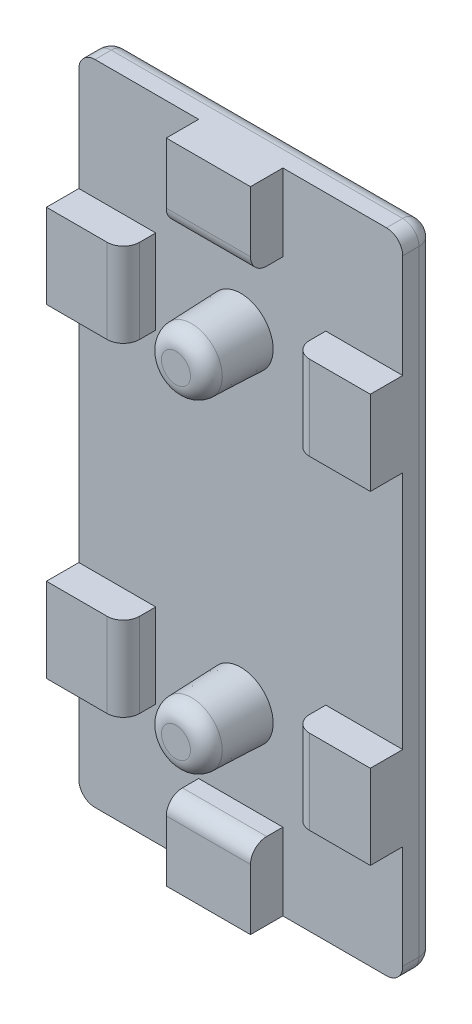
SolidWorks part; units mm, degrees
ref_plane "Front Plane" through (0, 0, 0) normal (0, 0, 1) x (1, 0, 0)
ref_plane "Top Plane" through (0, 0, 0) normal (0, 1, 0) x (1, 0, 0)
ref_plane "Right Plane" through (0, 0, 0) normal (1, 0, 0) x (0, 0, -1)
sketch "Sketch1" plane through (0, 0, 0) normal (0, 0, 1) x (1, 0, 0)
  line L1 (1, 0) -> (19, 0)
  line L2 (0, 1) -> (0, 39)
  line L3 (1, 40) -> (19, 40)
  line L4 (20, 1) -> (20, 39)
  arc A0 (1, 40) -> (0, 39) centre (1, 39) ccw
  arc A1 (1, 0) -> (0, 1) centre (1, 1) cw
  arc A2 (20, 1) -> (19, 0) centre (19, 1) cw
  arc A3 (20, 39) -> (19, 40) centre (19, 39) ccw
  point P7 (0, 40)
  point P10 (0, 0)
  point P13 (20, 0)
  dimension "D2" = 1
  dimension "D3" = 1
  dimension "D1" = 20
  dimension "40" = 40
extrude "Boss-Extrude1" add sketch "Sketch1" along normal blind 2
sketch "Sketch2" plane through (0, 0, 2) normal (0, 0, 1) x (1, 0, 0)
  line L0 (10, 30) -> (10, 10) construction
  line L1 (0, 39) -> (0, 1) construction
  line L2 (19, 40) -> (1, 40) construction
  circle A0 centre (10, 30) radius 2
  circle A1 centre (10, 10) radius 2
  point P4 (0, 20)
  point P5 (10, 20)
  point P8 (10, 40)
  dimension "D2" = 4
  dimension "D1" = 20
extrude "Boss-Extrude2" add sketch "Sketch2" along normal blind 4 draft 2
fillet "Fillet1" radius 1 8 edges at (0, 20, 0) (0.2929, 0.2929, 0) (10, 0, 0) (19.7071, 0.2929, 0) (20, 20, 0) (19.7071, 39.7071, 0) (10, 40, 0) (0.2929, 39.7071, 0)
sketch "Sketch4" plane through (0, 0, 2) normal (0, 0, 1) x (1, 0, 0)
  line L1 (7.4, 40) -> (12.6, 40)
  line L2 (7.4, 40) -> (7.4, 35.25)
  line L3 (7.4, 35.25) -> (12.6, 35.25)
  line L4 (12.6, 40) -> (12.6, 35.25)
  line L5 (1, 1) -> (19, 1) construction
  line L6 (7.4, 0) -> (12.6, 0)
  line L7 (7.4, 0) -> (7.4, 4.75)
  line L8 (7.4, 4.75) -> (12.6, 4.75)
  line L9 (12.6, 0) -> (12.6, 4.75)
  line L11 (0, 32.6) -> (4.75, 32.6)
  line L12 (0, 32.6) -> (0, 27.4)
  line L13 (0, 27.4) -> (4.75, 27.4)
  line L14 (4.75, 32.6) -> (4.75, 27.4)
  line L16 (0, 12.6) -> (4.75, 12.6)
  line L17 (0, 12.6) -> (0, 7.4)
  line L18 (0, 7.4) -> (4.75, 7.4)
  line L19 (4.75, 12.6) -> (4.75, 7.4)
  line L20 (20, 32.6) -> (15.25, 32.6)
  line L21 (20, 32.6) -> (20, 27.4)
  line L22 (20, 27.4) -> (15.25, 27.4)
  line L23 (15.25, 32.6) -> (15.25, 27.4)
  line L24 (20, 1) -> (20, 39) construction
  line L25 (20, 12.6) -> (15.25, 12.6)
  line L26 (20, 12.6) -> (20, 7.4)
  line L27 (20, 7.4) -> (15.25, 7.4)
  line L28 (15.25, 12.6) -> (15.25, 7.4)
  line L29 (1, 0) -> (19, 0) construction
  line L30 (19, 40) -> (1, 40) construction
  line L31 (0, 39) -> (0, 1) construction
  point P4 (0, 30)
  point P5 (0, 10)
  point P12 (10, 1)
  point P13 (10, 4.75)
  point P14 (10, 35.25)
  point P35 (4.75, 30)
  point P36 (15.25, 30)
  point P37 (4.75, 10)
  point P38 (15.25, 10)
  point P43 (10, 0)
  dimension "D1" = 5.2
  dimension "D2" = 4.75
  dimension "D3" = 10
  dimension "D4" = 10
extrude "Boss-Extrude3" add sketch "Sketch4" along normal blind 2
fillet "Fillet2" radius 1 8 edges at (11.8603, 30, 6) (11.8603, 10, 6) (4.75, 10, 4) (10, 4.75, 4) (15.25, 10, 4) (15.25, 30, 4) (4.75, 30, 4) (10, 35.25, 4)
sketch "Sketch5" plane through (0, 0, 0) normal (0, 0, -1) x (-1, 0, 0)
  line L4 (-14.8522, 26.4361) -> (-14.8354, 26.3871)
  line L5 (-14.8354, 26.3871) -> (-14.8168, 26.3393)
  line L6 (-14.8168, 26.3393) -> (-14.7964, 26.2926)
  line L7 (-14.7964, 26.2926) -> (-14.7743, 26.2469)
  line L8 (-14.7743, 26.2469) -> (-14.7506, 26.2022)
  line L9 (-14.7506, 26.2022) -> (-14.7254, 26.1584)
  line L10 (-14.7254, 26.1584) -> (-14.6988, 26.1156)
  line L11 (-14.6988, 26.1156) -> (-14.6708, 26.0736)
  line L12 (-14.6708, 26.0736) -> (-14.6415, 26.0325)
  line L13 (-14.6415, 26.0325) -> (-14.6111, 25.9921)
  line L14 (-14.6111, 25.9921) -> (-14.5795, 25.9525)
  line L15 (-14.5795, 25.9525) -> (-14.547, 25.9136)
  line L16 (-14.547, 25.9136) -> (-14.5135, 25.8754)
  line L17 (-14.5135, 25.8754) -> (-14.444, 25.8007)
  line L18 (-14.444, 25.8007) -> (-14.3348, 25.6925)
  line L19 (-14.3348, 25.6925) -> (-13.9175, 25.3179)
  line L20 (-13.9175, 25.3179) -> (-14.0057, 25.3264)
  line L21 (-14.0057, 25.3264) -> (-15.1851, 25.5154)
  line L22 (-15.1851, 25.5154) -> (-15.2295, 25.5221)
  line L23 (-15.2295, 25.5221) -> (-15.2735, 25.5301)
  line L24 (-15.2735, 25.5301) -> (-15.3171, 25.5393)
  line L25 (-15.3171, 25.5393) -> (-15.3604, 25.5495)
  line L26 (-15.3604, 25.5495) -> (-15.4459, 25.5731)
  line L27 (-15.4459, 25.5731) -> (-15.5302, 25.6003)
  line L28 (-15.5302, 25.6003) -> (-15.6549, 25.6466)
  line L29 (-15.6549, 25.6466) -> (-16.2255, 25.897)
  line L30 (-16.2255, 25.897) -> (-16.3909, 25.9613)
  line L31 (-16.3909, 25.9613) -> (-16.3834, 25.9188)
  line L32 (-16.3834, 25.9188) -> (-16.3738, 25.8773)
  line L33 (-16.3738, 25.8773) -> (-16.3622, 25.837)
  line L34 (-16.3622, 25.837) -> (-16.3486, 25.7976)
  line L35 (-16.3486, 25.7976) -> (-16.3333, 25.7592)
  line L36 (-16.3333, 25.7592) -> (-16.3162, 25.7217)
  line L37 (-16.3162, 25.7217) -> (-16.2976, 25.6851)
  line L38 (-16.2976, 25.6851) -> (-16.2774, 25.6493)
  line L39 (-16.2774, 25.6493) -> (-16.2558, 25.6142)
  line L40 (-16.2558, 25.6142) -> (-16.233, 25.5799)
  line L41 (-16.233, 25.5799) -> (-16.2089, 25.5463)
  line L42 (-16.2089, 25.5463) -> (-16.1837, 25.5133)
  line L43 (-16.1837, 25.5133) -> (-16.1305, 25.449)
  line L44 (-16.1305, 25.449) -> (-16.0741, 25.3866)
  line L45 (-16.0741, 25.3866) -> (-15.955, 25.2664)
  line L46 (-15.955, 25.2664) -> (-15.6862, 25.0036)
  line L47 (-15.6862, 25.0036) -> (-15.8048, 25.0311)
  line L48 (-15.8048, 25.0311) -> (-16.04, 25.0934)
  line L49 (-16.04, 25.0934) -> (-16.2725, 25.1645)
  line L50 (-16.2725, 25.1645) -> (-16.6167, 25.2853)
  line L51 (-16.6167, 25.2853) -> (-17.3469, 25.5884)
  line L52 (-17.3469, 25.5884) -> (-17.3442, 25.5634)
  line L53 (-17.3442, 25.5634) -> (-17.3362, 25.5141)
  line L54 (-17.3362, 25.5141) -> (-17.3248, 25.4659)
  line L55 (-17.3248, 25.4659) -> (-17.3102, 25.4187)
  line L56 (-17.3102, 25.4187) -> (-17.283, 25.3498)
  line L57 (-17.283, 25.3498) -> (-17.2501, 25.2832)
  line L58 (-17.2501, 25.2832) -> (-17.1851, 25.177)
  line L59 (-17.1851, 25.177) -> (-17.0139, 24.9638)
  line L60 (-17.0139, 24.9638) -> (-16.4213, 24.4238)
  line L61 (-16.4213, 24.4238) -> (-16.1737, 24.2448)
  line L62 (-16.1737, 24.2448) -> (-15.8649, 24.0097)
  line L63 (-15.8649, 24.0097) -> (-16.8235, 24.219)
  line L64 (-16.8235, 24.219) -> (-17.3989, 24.329)
  line L65 (-17.3989, 24.329) -> (-17.3692, 24.2761)
  line L66 (-17.3692, 24.2761) -> (-17.3372, 24.2255)
  line L67 (-17.3372, 24.2255) -> (-17.303, 24.1771)
  line L68 (-17.303, 24.1771) -> (-17.2668, 24.1308)
  line L69 (-17.2668, 24.1308) -> (-17.2287, 24.0865)
  line L70 (-17.2287, 24.0865) -> (-17.1888, 24.0441)
  line L71 (-17.1888, 24.0441) -> (-17.1472, 24.0035)
  line L72 (-17.1472, 24.0035) -> (-17.1041, 23.9646)
  line L73 (-17.1041, 23.9646) -> (-17.0594, 23.9272)
  line L74 (-17.0594, 23.9272) -> (-17.0134, 23.8913)
  line L75 (-17.0134, 23.8913) -> (-16.9662, 23.8568)
  line L76 (-16.9662, 23.8568) -> (-16.9179, 23.8235)
  line L77 (-16.9179, 23.8235) -> (-16.8685, 23.7913)
  line L78 (-16.8685, 23.7913) -> (-16.8183, 23.7602)
  line L79 (-16.8183, 23.7602) -> (-16.7155, 23.7006)
  line L80 (-16.7155, 23.7006) -> (-16.5576, 23.6161)
  line L81 (-16.5576, 23.6161) -> (-16.1352, 23.3998)
  line L82 (-16.1352, 23.3998) -> (-16.0342, 23.343)
  line L83 (-16.0342, 23.343) -> (-16.4665, 23.2918)
  line L84 (-16.4665, 23.2918) -> (-16.4541, 23.272)
  line L85 (-16.4541, 23.272) -> (-16.4271, 23.2347)
  line L86 (-16.4271, 23.2347) -> (-16.3974, 23.2002)
  line L87 (-16.3974, 23.2002) -> (-16.3653, 23.1684)
  line L88 (-16.3653, 23.1684) -> (-16.3309, 23.1391)
  line L89 (-16.3309, 23.1391) -> (-16.2757, 23.0993)
  line L90 (-16.2757, 23.0993) -> (-16.1968, 23.0531)
  line L91 (-16.1968, 23.0531) -> (-15.9217, 22.9399)
  line L92 (-15.9217, 22.9399) -> (-15.8372, 22.9134)
  line L93 (-15.8372, 22.9134) -> (-14.6718, 22.6494)
  line L94 (-14.6718, 22.6494) -> (-14.9108, 22.492)
  line L95 (-14.9108, 22.492) -> (-14.7862, 22.4701)
  line L96 (-14.7862, 22.4701) -> (-14.1586, 22.3696)
  line L97 (-14.1586, 22.3696) -> (-14.0353, 22.3402)
  line L98 (-14.0353, 22.3402) -> (-13.954, 22.317)
  line L99 (-13.954, 22.317) -> (-13.8736, 22.2903)
  line L100 (-13.8736, 22.2903) -> (-13.7943, 22.2597)
  line L101 (-13.7943, 22.2597) -> (-13.755, 22.2428)
  line L102 (-13.755, 22.2428) -> (-13.7161, 22.2247)
  line L103 (-13.7161, 22.2247) -> (-13.8147, 22.1244)
  line L104 (-13.8147, 22.1244) -> (-13.6483, 21.9581)
  line L105 (-13.6483, 21.9581) -> (-13.558, 21.8975)
  line L106 (-13.558, 21.8975) -> (-13.5009, 21.8721)
  line L107 (-13.5009, 21.8721) -> (-13.455, 21.8585)
  line L108 (-13.455, 21.8585) -> (-13.4253, 21.8514)
  line L109 (-13.4253, 21.8514) -> (-13.3356, 21.8344)
  line L110 (-13.3356, 21.8344) -> (-13.185, 21.8172)
  line L111 (-13.185, 21.8172) -> (-12.5777, 21.788)
  line L112 (-12.5777, 21.788) -> (-12.6596, 21.6424)
  line L113 (-12.6596, 21.6424) -> (-12.5986, 21.6186)
  line L114 (-12.5986, 21.6186) -> (-12.4745, 21.5783)
  line L115 (-12.4745, 21.5783) -> (-12.3481, 21.5471)
  line L116 (-12.3481, 21.5471) -> (-12.1878, 21.5201)
  line L117 (-12.1878, 21.5201) -> (-11.993, 21.5035)
  line L118 (-11.993, 21.5035) -> (-11.7321, 21.5049)
  line L119 (-11.7321, 21.5049) -> (-11.7028, 21.3666)
  line L120 (-11.7028, 21.3666) -> (-11.6815, 21.3337)
  line L121 (-11.6815, 21.3337) -> (-11.6629, 21.3183)
  line L122 (-11.6629, 21.3183) -> (-11.6476, 21.3104)
  line L123 (-11.6476, 21.3104) -> (-11.6298, 21.3046)
  line L124 (-11.6298, 21.3046) -> (-11.6078, 21.2998)
  line L125 (-11.6078, 21.2998) -> (-11.564, 21.2935)
  line L126 (-11.564, 21.2935) -> (-11.5204, 21.2912)
  line L127 (-11.5204, 21.2912) -> (-11.4769, 21.2926)
  line L128 (-11.4769, 21.2926) -> (-11.4337, 21.2972)
  line L129 (-11.4337, 21.2972) -> (-11.3479, 21.3145)
  line L130 (-11.3479, 21.3145) -> (-11.0158, 21.4351)
  line L131 (-11.0158, 21.4351) -> (-11.097, 21.2168)
  line L132 (-11.097, 21.2168) -> (-10.2297, 21.2244)
  line L133 (-10.2297, 21.2244) -> (-10.1966, 21.2219)
  line L134 (-10.1966, 21.2219) -> (-10.1639, 21.218)
  line L135 (-10.1639, 21.218) -> (-10.1315, 21.2129)
  line L136 (-10.1315, 21.2129) -> (-10.0996, 21.2064)
  line L137 (-10.0996, 21.2064) -> (-10.068, 21.1988)
  line L138 (-10.068, 21.1988) -> (-10.0369, 21.1899)
  line L139 (-10.0369, 21.1899) -> (-10.0062, 21.18)
  line L140 (-10.0062, 21.18) -> (-9.9759, 21.1689)
  line L141 (-9.9759, 21.1689) -> (-9.946, 21.1567)
  line L142 (-9.946, 21.1567) -> (-9.9165, 21.1435)
  line L143 (-9.9165, 21.1435) -> (-9.859, 21.1142)
  line L144 (-9.859, 21.1142) -> (-9.8032, 21.0813)
  line L145 (-9.8032, 21.0813) -> (-9.7493, 21.045)
  line L146 (-9.7493, 21.045) -> (-9.6974, 21.0057)
  line L147 (-9.6974, 21.0057) -> (-9.6474, 20.9636)
  line L148 (-9.6474, 20.9636) -> (-9.5763, 20.8962)
  line L149 (-9.5763, 20.8962) -> (-9.5098, 20.8244)
  line L150 (-9.5098, 20.8244) -> (-9.4483, 20.7493)
  line L151 (-9.4483, 20.7493) -> (-9.7849, 20.6834)
  line L152 (-9.7849, 20.6834) -> (-9.8366, 20.6915)
  line L153 (-9.8366, 20.6915) -> (-9.8879, 20.7011)
  line L154 (-9.8879, 20.7011) -> (-9.9389, 20.712)
  line L155 (-9.9389, 20.712) -> (-9.9896, 20.724)
  line L156 (-9.9896, 20.724) -> (-10.0901, 20.7512)
  line L157 (-10.0901, 20.7512) -> (-10.2391, 20.7982)
  line L158 (-10.2391, 20.7982) -> (-10.781, 20.9879)
  line L159 (-10.781, 20.9879) -> (-10.8807, 21.0176)
  line L160 (-10.8807, 21.0176) -> (-10.9813, 21.0437)
  line L161 (-10.9813, 21.0437) -> (-11.0321, 21.0551)
  line L162 (-11.0321, 21.0551) -> (-11.0832, 21.0653)
  line L163 (-11.0832, 21.0653) -> (-11.1346, 21.0741)
  line L164 (-11.1346, 21.0741) -> (-11.1864, 21.0814)
  line L165 (-11.1864, 21.0814) -> (-11.2386, 21.0871)
  line L166 (-11.2386, 21.0871) -> (-11.2819, 21.0917)
  line L167 (-11.2819, 21.0917) -> (-11.3686, 21.0986)
  line L168 (-11.3686, 21.0986) -> (-11.4557, 21.1021)
  line L169 (-11.4557, 21.1021) -> (-11.5428, 21.1022)
  line L170 (-11.5428, 21.1022) -> (-11.6299, 21.0989)
  line L171 (-11.6299, 21.0989) -> (-11.7167, 21.0921)
  line L172 (-11.7167, 21.0921) -> (-11.8032, 21.0818)
  line L173 (-11.8032, 21.0818) -> (-11.8891, 21.0679)
  line L174 (-11.8891, 21.0679) -> (-11.9743, 21.0504)
  line L175 (-11.9743, 21.0504) -> (-12.0587, 21.0293)
  line L176 (-12.0587, 21.0293) -> (-12.142, 21.0045)
  line L177 (-12.142, 21.0045) -> (-12.2242, 20.976)
  line L178 (-12.2242, 20.976) -> (-12.305, 20.9437)
  line L179 (-12.305, 20.9437) -> (-12.3842, 20.9075)
  line L180 (-12.3842, 20.9075) -> (-12.4619, 20.8675)
  line L181 (-12.4619, 20.8675) -> (-12.6506, 20.7633)
  line L182 (-12.6506, 20.7633) -> (-12.775, 20.6903)
  line L183 (-12.775, 20.6903) -> (-12.8978, 20.6144)
  line L184 (-12.8978, 20.6144) -> (-13.0188, 20.5354)
  line L185 (-13.0188, 20.5354) -> (-13.1376, 20.4532)
  line L186 (-13.1376, 20.4532) -> (-13.2539, 20.3676)
  line L187 (-13.2539, 20.3676) -> (-13.311, 20.3235)
  line L188 (-13.311, 20.3235) -> (-13.3673, 20.2786)
  line L189 (-13.3673, 20.2786) -> (-13.4229, 20.2327)
  line L190 (-13.4229, 20.2327) -> (-13.4776, 20.1859)
  line L191 (-13.4776, 20.1859) -> (-13.5315, 20.1381)
  line L192 (-13.5315, 20.1381) -> (-13.5845, 20.0894)
  line L193 (-13.5845, 20.0894) -> (-13.6365, 20.0397)
  line L194 (-13.6365, 20.0397) -> (-13.6875, 19.989)
  line L195 (-13.6875, 19.989) -> (-13.7376, 19.9373)
  line L196 (-13.7376, 19.9373) -> (-13.7865, 19.8846)
  line L197 (-13.7865, 19.8846) -> (-13.8343, 19.8309)
  line L198 (-13.8343, 19.8309) -> (-13.881, 19.7761)
  line L199 (-13.881, 19.7761) -> (-13.9266, 19.7202)
  line L200 (-13.9266, 19.7202) -> (-13.9709, 19.6632)
  line L201 (-13.9709, 19.6632) -> (-14.0139, 19.6051)
  line L202 (-14.0139, 19.6051) -> (-14.0556, 19.5458)
  line L203 (-14.0556, 19.5458) -> (-14.6185, 18.7464)
  line L204 (-14.6185, 18.7464) -> (-14.6508, 18.6959)
  line L205 (-14.6508, 18.6959) -> (-15.1536, 18.0649)
  line L206 (-15.1536, 18.0649) -> (-15.2703, 17.9205)
  line L207 (-15.2703, 17.9205) -> (-15.3916, 17.7801)
  line L208 (-15.3916, 17.7801) -> (-15.5599, 17.5988)
  line L209 (-15.5599, 17.5988) -> (-15.7352, 17.4241)
  line L210 (-15.7352, 17.4241) -> (-15.9167, 17.2559)
  line L211 (-15.9167, 17.2559) -> (-16.1515, 17.0544)
  line L212 (-16.1515, 17.0544) -> (-16.443, 16.8248)
  line L213 (-16.443, 16.8248) -> (-16.6092, 16.7094)
  line L214 (-16.6092, 16.7094) -> (-16.6934, 16.6698)
  line L215 (-16.6934, 16.6698) -> (-16.7451, 16.658)
  line L216 (-16.7451, 16.658) -> (-16.7861, 16.6559)
  line L217 (-16.7861, 16.6559) -> (-16.8054, 16.6552)
  line L218 (-16.8054, 16.6552) -> (-16.8245, 16.6559)
  line L219 (-16.8245, 16.6559) -> (-16.8434, 16.6577)
  line L220 (-16.8434, 16.6577) -> (-16.8807, 16.6644)
  line L221 (-16.8807, 16.6644) -> (-16.9176, 16.6746)
  line L222 (-16.9176, 16.6746) -> (-17.1163, 16.7524)
  line L223 (-17.1163, 16.7524) -> (-17.171, 16.7674)
  line L224 (-17.171, 16.7674) -> (-17.2081, 16.7731)
  line L225 (-17.2081, 16.7731) -> (-17.2268, 16.7742)
  line L226 (-17.2268, 16.7742) -> (-17.2457, 16.7741)
  line L227 (-17.2457, 16.7741) -> (-17.2648, 16.7726)
  line L228 (-17.2648, 16.7726) -> (-17.284, 16.7697)
  line L229 (-17.284, 16.7697) -> (-17.3035, 16.7651)
  line L230 (-17.3035, 16.7651) -> (-17.3232, 16.7589)
  line L231 (-17.3232, 16.7589) -> (-17.9667, 16.5375)
  line L232 (-17.9667, 16.5375) -> (-17.9384, 16.4163)
  line L233 (-17.9384, 16.4163) -> (-18.3891, 16.2415)
  line L234 (-18.3891, 16.2415) -> (-18.2583, 16.1389)
  line L235 (-18.2583, 16.1389) -> (-18.5279, 15.8963)
  line L236 (-18.5279, 15.8963) -> (-18.4036, 15.808)
  line L237 (-18.4036, 15.808) -> (-18.4293, 15.7476)
  line L238 (-18.4293, 15.7476) -> (-18.5059, 15.4981)
  line L239 (-18.5059, 15.4981) -> (-18.529, 15.326)
  line L240 (-18.529, 15.326) -> (-18.5286, 15.1945)
  line L241 (-18.5286, 15.1945) -> (-18.3402, 15.1883)
  line L242 (-18.3402, 15.1883) -> (-18.0785, 14.917)
  line L243 (-18.0785, 14.917) -> (-18.0326, 15.0164)
  line L244 (-18.0326, 15.0164) -> (-17.9458, 15.1995)
  line L245 (-17.9458, 15.1995) -> (-17.9145, 15.243)
  line L246 (-17.9145, 15.243) -> (-17.8905, 15.2691)
  line L247 (-17.8905, 15.2691) -> (-17.8636, 15.2925)
  line L248 (-17.8636, 15.2925) -> (-17.8488, 15.3031)
  line L249 (-17.8488, 15.3031) -> (-17.8332, 15.3129)
  line L250 (-17.8332, 15.3129) -> (-17.8167, 15.3218)
  line L251 (-17.8167, 15.3218) -> (-17.7991, 15.3298)
  line L252 (-17.7991, 15.3298) -> (-17.7805, 15.3368)
  line L253 (-17.7805, 15.3368) -> (-17.7402, 15.1527)
  line L254 (-17.7402, 15.1527) -> (-17.6804, 15.1654)
  line L255 (-17.6804, 15.1654) -> (-17.5467, 15.2102)
  line L256 (-17.5467, 15.2102) -> (-17.2156, 15.4025)
  line L257 (-17.2156, 15.4025) -> (-17.0558, 15.3487)
  line L258 (-17.0558, 15.3487) -> (-16.9674, 15.3474)
  line L259 (-16.9674, 15.3474) -> (-16.9341, 15.3626)
  line L260 (-16.9341, 15.3626) -> (-16.8561, 15.4083)
  line L261 (-16.8561, 15.4083) -> (-16.5665, 15.6811)
  line L262 (-16.5665, 15.6811) -> (-16.5493, 15.7)
  line L263 (-16.5493, 15.7) -> (-16.4953, 15.7535)
  line L264 (-16.4953, 15.7535) -> (-16.3981, 15.8339)
  line L265 (-16.3981, 15.8339) -> (-15.9832, 16.1244)
  line L266 (-15.9832, 16.1244) -> (-15.9134, 16.1765)
  line L267 (-15.9134, 16.1765) -> (-15.8445, 16.2296)
  line L268 (-15.8445, 16.2296) -> (-15.7766, 16.2838)
  line L269 (-15.7766, 16.2838) -> (-15.7096, 16.3389)
  line L270 (-15.7096, 16.3389) -> (-15.6434, 16.3951)
  line L271 (-15.6434, 16.3951) -> (-15.5781, 16.4521)
  line L272 (-15.5781, 16.4521) -> (-15.5137, 16.5101)
  line L273 (-15.5137, 16.5101) -> (-15.45, 16.5689)
  line L274 (-15.45, 16.5689) -> (-15.3871, 16.6286)
  line L275 (-15.3871, 16.6286) -> (-15.2635, 16.7501)
  line L276 (-15.2635, 16.7501) -> (-15.1426, 16.8745)
  line L277 (-15.1426, 16.8745) -> (-15.0242, 17.0015)
  line L278 (-15.0242, 17.0015) -> (-14.9081, 17.1306)
  line L279 (-14.9081, 17.1306) -> (-14.7378, 17.3278)
  line L280 (-14.7378, 17.3278) -> (-14.2469, 17.9355)
  line L281 (-14.2469, 17.9355) -> (-14.2159, 17.9678)
  line L282 (-14.2159, 17.9678) -> (-14.156, 18.0341)
  line L283 (-14.156, 18.0341) -> (-14.0707, 18.137)
  line L284 (-14.0707, 18.137) -> (-13.9116, 18.3515)
  line L285 (-13.9116, 18.3515) -> (-13.5481, 18.8585)
  line L286 (-13.5481, 18.8585) -> (-13.4621, 18.9611)
  line L287 (-13.4621, 18.9611) -> (-13.4404, 18.5924)
  line L288 (-13.4404, 18.5924) -> (-13.4508, 18.5062)
  line L289 (-13.4508, 18.5062) -> (-13.4642, 18.4553)
  line L290 (-13.4642, 18.4553) -> (-13.548, 18.3448)
  line L291 (-13.548, 18.3448) -> (-14.1691, 17.5969)
  line L292 (-14.1691, 17.5969) -> (-14.306, 17.4106)
  line L293 (-14.306, 17.4106) -> (-14.329, 17.374)
  line L294 (-14.329, 17.374) -> (-14.3495, 17.3368)
  line L295 (-14.3495, 17.3368) -> (-14.3676, 17.2991)
  line L296 (-14.3676, 17.2991) -> (-14.3833, 17.261)
  line L297 (-14.3833, 17.261) -> (-14.397, 17.2224)
  line L298 (-14.397, 17.2224) -> (-14.4085, 17.1833)
  line L299 (-14.4085, 17.1833) -> (-14.4182, 17.1439)
  line L300 (-14.4182, 17.1439) -> (-14.426, 17.104)
  line L301 (-14.426, 17.104) -> (-14.4322, 17.0639)
  line L302 (-14.4322, 17.0639) -> (-14.4369, 17.0234)
  line L303 (-14.4369, 17.0234) -> (-14.4401, 16.9827)
  line L304 (-14.4401, 16.9827) -> (-14.442, 16.9417)
  line L305 (-14.442, 16.9417) -> (-14.4424, 16.8591)
  line L306 (-14.4424, 16.8591) -> (-14.4363, 16.7342)
  line L307 (-14.4363, 16.7342) -> (-14.3978, 16.3188)
  line L308 (-14.3978, 16.3188) -> (-14.3941, 16.2377)
  line L309 (-14.3941, 16.2377) -> (-14.4677, 15.4302)
  line L310 (-14.4677, 15.4302) -> (-14.481, 15.3327)
  line L311 (-14.481, 15.3327) -> (-14.5371, 14.9645)
  line L312 (-14.5371, 14.9645) -> (-14.5383, 14.8908)
  line L313 (-14.5383, 14.8908) -> (-14.5352, 14.8418)
  line L314 (-14.5352, 14.8418) -> (-14.5287, 14.7929)
  line L315 (-14.5287, 14.7929) -> (-14.5181, 14.7441)
  line L316 (-14.5181, 14.7441) -> (-14.5112, 14.7197)
  line L317 (-14.5112, 14.7197) -> (-14.5048, 14.7019)
  line L318 (-14.5048, 14.7019) -> (-14.4974, 14.6849)
  line L319 (-14.4974, 14.6849) -> (-14.4892, 14.6687)
  line L320 (-14.4892, 14.6687) -> (-14.4704, 14.6384)
  line L321 (-14.4704, 14.6384) -> (-14.4487, 14.6106)
  line L322 (-14.4487, 14.6106) -> (-14.4245, 14.585)
  line L323 (-14.4245, 14.585) -> (-14.3558, 14.5283)
  line L324 (-14.3558, 14.5283) -> (-14.1321, 14.375)
  line L325 (-14.1321, 14.375) -> (-14.0711, 14.3267)
  line L326 (-14.0711, 14.3267) -> (-13.8682, 14.1371)
  line L327 (-13.8682, 14.1371) -> (-13.8204, 14.1042)
  line L328 (-13.8204, 14.1042) -> (-13.7866, 14.0858)
  line L329 (-13.7866, 14.0858) -> (-13.7509, 14.071)
  line L330 (-13.7509, 14.071) -> (-13.7323, 14.0651)
  line L331 (-13.7323, 14.0651) -> (-13.713, 14.0602)
  line L332 (-13.713, 14.0602) -> (-13.6932, 14.0565)
  line L333 (-13.6932, 14.0565) -> (-13.6727, 14.0541)
  line L334 (-13.6727, 14.0541) -> (-13.6307, 14.051)
  line L335 (-13.6307, 14.051) -> (-12.4525, 14.0515)
  line L336 (-12.4525, 14.0515) -> (-12.4236, 14.0541)
  line L337 (-12.4236, 14.0541) -> (-12.3284, 14.0836)
  line L338 (-12.3284, 14.0836) -> (-12.2805, 14.1175)
  line L339 (-12.2805, 14.1175) -> (-12.2559, 14.1473)
  line L340 (-12.2559, 14.1473) -> (-12.2426, 14.1735)
  line L341 (-12.2426, 14.1735) -> (-12.2345, 14.2031)
  line L342 (-12.2345, 14.2031) -> (-12.2192, 14.4073)
  line L343 (-12.2192, 14.4073) -> (-12.2256, 14.4753)
  line L344 (-12.2256, 14.4753) -> (-12.237, 14.5242)
  line L345 (-12.237, 14.5242) -> (-12.2482, 14.5553)
  line L346 (-12.2482, 14.5553) -> (-12.2628, 14.585)
  line L347 (-12.2628, 14.585) -> (-12.281, 14.6129)
  line L348 (-12.281, 14.6129) -> (-12.2916, 14.6262)
  line L349 (-12.2916, 14.6262) -> (-12.3033, 14.6389)
  line L350 (-12.3033, 14.6389) -> (-12.316, 14.6511)
  line L351 (-12.316, 14.6511) -> (-12.3298, 14.6627)
  line L352 (-12.3298, 14.6627) -> (-12.352, 14.6836)
  line L353 (-12.352, 14.6836) -> (-12.3749, 14.7033)
  line L354 (-12.3749, 14.7033) -> (-12.3986, 14.7219)
  line L355 (-12.3986, 14.7219) -> (-12.4229, 14.7394)
  line L356 (-12.4229, 14.7394) -> (-12.4479, 14.7557)
  line L357 (-12.4479, 14.7557) -> (-12.4734, 14.7708)
  line L358 (-12.4734, 14.7708) -> (-12.4995, 14.7849)
  line L359 (-12.4995, 14.7849) -> (-12.5261, 14.7979)
  line L360 (-12.5261, 14.7979) -> (-12.5531, 14.8097)
  line L361 (-12.5531, 14.8097) -> (-12.5806, 14.8205)
  line L362 (-12.5806, 14.8205) -> (-12.6085, 14.8301)
  line L363 (-12.6085, 14.8301) -> (-12.6368, 14.8387)
  line L364 (-12.6368, 14.8387) -> (-12.6654, 14.8462)
  line L365 (-12.6654, 14.8462) -> (-12.6943, 14.8526)
  line L366 (-12.6943, 14.8526) -> (-12.7234, 14.858)
  line L367 (-12.7234, 14.858) -> (-12.7823, 14.8656)
  line L368 (-12.7823, 14.8656) -> (-12.8417, 14.869)
  line L369 (-12.8417, 14.869) -> (-12.9013, 14.8684)
  line L370 (-12.9013, 14.8684) -> (-12.9609, 14.8638)
  line L371 (-12.9609, 14.8638) -> (-13.0201, 14.8552)
  line L372 (-13.0201, 14.8552) -> (-13.0786, 14.8426)
  line L373 (-13.0786, 14.8426) -> (-13.1361, 14.8263)
  line L374 (-13.1361, 14.8263) -> (-13.3389, 15.2799)
  line L375 (-13.3389, 15.2799) -> (-13.1168, 15.6033)
  line L376 (-13.1168, 15.6033) -> (-13.0124, 15.7899)
  line L377 (-13.0124, 15.7899) -> (-12.9525, 15.919)
  line L378 (-12.9525, 15.919) -> (-12.9134, 16.0184)
  line L379 (-12.9134, 16.0184) -> (-12.8802, 16.1202)
  line L380 (-12.8802, 16.1202) -> (-12.8616, 16.1894)
  line L381 (-12.8616, 16.1894) -> (-12.7761, 16.5094)
  line L382 (-12.7761, 16.5094) -> (-12.2776, 16.6874)
  line L383 (-12.2776, 16.6874) -> (-12.2367, 16.7024)
  line L384 (-12.2367, 16.7024) -> (-12.1097, 16.735)
  line L385 (-12.1097, 16.735) -> (-11.8101, 16.7993)
  line L386 (-11.8101, 16.7993) -> (-11.7494, 16.8226)
  line L387 (-11.7494, 16.8226) -> (-11.7102, 16.8419)
  line L388 (-11.7102, 16.8419) -> (-11.6724, 16.8647)
  line L389 (-11.6724, 16.8647) -> (-11.629, 16.9032)
  line L390 (-11.629, 16.9032) -> (-11.5278, 17.0064)
  line L391 (-11.5278, 17.0064) -> (-11.1469, 17.5167)
  line L392 (-11.1469, 17.5167) -> (-11.0279, 17.473)
  line L393 (-11.0279, 17.473) -> (-10.9035, 17.406)
  line L394 (-10.9035, 17.406) -> (-10.8554, 17.3668)
  line L395 (-10.8554, 17.3668) -> (-10.8234, 17.3325)
  line L396 (-10.8234, 17.3325) -> (-10.7955, 17.2936)
  line L397 (-10.7955, 17.2936) -> (-10.7796, 17.2647)
  line L398 (-10.7796, 17.2647) -> (-10.9043, 16.9146)
  line L399 (-10.9043, 16.9146) -> (-11.0365, 16.4891)
  line L400 (-11.0365, 16.4891) -> (-11.0676, 16.3438)
  line L401 (-11.0676, 16.3438) -> (-11.0846, 16.2332)
  line L402 (-11.0846, 16.2332) -> (-11.0916, 16.1824)
  line L403 (-11.0916, 16.1824) -> (-11.1247, 15.8917)
  line L404 (-11.1247, 15.8917) -> (-11.1244, 15.8124)
  line L405 (-11.1244, 15.8124) -> (-11.1201, 15.7604)
  line L406 (-11.1201, 15.7604) -> (-11.112, 15.7093)
  line L407 (-11.112, 15.7093) -> (-11.1063, 15.6842)
  line L408 (-11.1063, 15.6842) -> (-11.0994, 15.6594)
  line L409 (-11.0994, 15.6594) -> (-11.0913, 15.6349)
  line L410 (-11.0913, 15.6349) -> (-11.0818, 15.6108)
  line L411 (-11.0818, 15.6108) -> (-11.071, 15.5871)
  line L412 (-11.071, 15.5871) -> (-11.0587, 15.5639)
  line L413 (-11.0587, 15.5639) -> (-11.0449, 15.5411)
  line L414 (-11.0449, 15.5411) -> (-11.0295, 15.5188)
  line L415 (-11.0295, 15.5188) -> (-11.0125, 15.497)
  line L416 (-11.0125, 15.497) -> (-10.9858, 15.4651)
  line L417 (-10.9858, 15.4651) -> (-10.9029, 15.3723)
  line L418 (-10.9029, 15.3723) -> (-10.7558, 15.2264)
  line L419 (-10.7558, 15.2264) -> (-10.1297, 14.6811)
  line L420 (-10.1297, 14.6811) -> (-9.8015, 14.2696)
  line L421 (-9.8015, 14.2696) -> (-9.6602, 14.1279)
  line L422 (-9.6602, 14.1279) -> (-9.5531, 14.0989)
  line L423 (-9.5531, 14.0989) -> (-9.0215, 14.0455)
  line L424 (-9.0215, 14.0455) -> (-8.7186, 14.0442)
  line L425 (-8.7186, 14.0442) -> (-8.5926, 14.0575)
  line L426 (-8.5926, 14.0575) -> (-8.5188, 14.0725)
  line L427 (-8.5188, 14.0725) -> (-8.4707, 14.0862)
  line L428 (-8.4707, 14.0862) -> (-8.4238, 14.103)
  line L429 (-8.4238, 14.103) -> (-8.3781, 14.1235)
  line L430 (-8.3781, 14.1235) -> (-8.3339, 14.1478)
  line L431 (-8.3339, 14.1478) -> (-8.3124, 14.1615)
  line L432 (-8.3124, 14.1615) -> (-8.2969, 14.1919)
  line L433 (-8.2969, 14.1919) -> (-8.2791, 14.2396)
  line L434 (-8.2791, 14.2396) -> (-8.2674, 14.2892)
  line L435 (-8.2674, 14.2892) -> (-8.2605, 14.3573)
  line L436 (-8.2605, 14.3573) -> (-8.2627, 14.4263)
  line L437 (-8.2627, 14.4263) -> (-8.281, 14.5287)
  line L438 (-8.281, 14.5287) -> (-8.321, 14.6404)
  line L439 (-8.321, 14.6404) -> (-8.3335, 14.6544)
  line L440 (-8.3335, 14.6544) -> (-8.3466, 14.6673)
  line L441 (-8.3466, 14.6673) -> (-8.3603, 14.6793)
  line L442 (-8.3603, 14.6793) -> (-8.3892, 14.7004)
  line L443 (-8.3892, 14.7004) -> (-8.42, 14.7182)
  line L444 (-8.42, 14.7182) -> (-8.4524, 14.7329)
  line L445 (-8.4524, 14.7329) -> (-8.5211, 14.7551)
  line L446 (-8.5211, 14.7551) -> (-8.8098, 14.8066)
  line L447 (-8.8098, 14.8066) -> (-8.8325, 14.809)
  line L448 (-8.8325, 14.809) -> (-8.8545, 14.8126)
  line L449 (-8.8545, 14.8126) -> (-8.8759, 14.8174)
  line L450 (-8.8759, 14.8174) -> (-8.8968, 14.8232)
  line L451 (-8.8968, 14.8232) -> (-8.9369, 14.838)
  line L452 (-8.9369, 14.838) -> (-8.9752, 14.8563)
  line L453 (-8.9752, 14.8563) -> (-9.0298, 14.8894)
  line L454 (-9.0298, 14.8894) -> (-9.2307, 15.0549)
  line L455 (-9.2307, 15.0549) -> (-9.3337, 15.1327)
  line L456 (-9.3337, 15.1327) -> (-9.5198, 15.2639)
  line L457 (-9.5198, 15.2639) -> (-9.5575, 15.3046)
  line L458 (-9.5575, 15.3046) -> (-9.5803, 15.3392)
  line L459 (-9.5803, 15.3392) -> (-9.5923, 15.3645)
  line L460 (-9.5923, 15.3645) -> (-9.6013, 15.3918)
  line L461 (-9.6013, 15.3918) -> (-9.6071, 15.4213)
  line L462 (-9.6071, 15.4213) -> (-9.6163, 15.4525)
  line L463 (-9.6163, 15.4525) -> (-9.6239, 15.4837)
  line L464 (-9.6239, 15.4837) -> (-9.6301, 15.5148)
  line L465 (-9.6301, 15.5148) -> (-9.6349, 15.546)
  line L466 (-9.6349, 15.546) -> (-9.6383, 15.5771)
  line L467 (-9.6383, 15.5771) -> (-9.6405, 15.6083)
  line L468 (-9.6405, 15.6083) -> (-9.6415, 15.6394)
  line L469 (-9.6415, 15.6394) -> (-9.6414, 15.6705)
  line L470 (-9.6414, 15.6705) -> (-9.6381, 15.7327)
  line L471 (-9.6381, 15.7327) -> (-9.6311, 15.7947)
  line L472 (-9.6311, 15.7947) -> (-9.6151, 15.8876)
  line L473 (-9.6151, 15.8876) -> (-9.5023, 16.3147)
  line L474 (-9.5023, 16.3147) -> (-9.4883, 16.3593)
  line L475 (-9.4883, 16.3593) -> (-9.471, 16.402)
  line L476 (-9.471, 16.402) -> (-9.4397, 16.4631)
  line L477 (-9.4397, 16.4631) -> (-9.3639, 16.578)
  line L478 (-9.3639, 16.578) -> (-9.1914, 16.823)
  line L479 (-9.1914, 16.823) -> (-9.1602, 16.8846)
  line L480 (-9.1602, 16.8846) -> (-9.0205, 17.1883)
  line L481 (-9.0205, 17.1883) -> (-8.9607, 17.1752)
  line L482 (-8.9607, 17.1752) -> (-8.7559, 17.1148)
  line L483 (-8.7559, 17.1148) -> (-8.1793, 16.9145)
  line L484 (-8.1793, 16.9145) -> (-8.032, 16.8673)
  line L485 (-8.032, 16.8673) -> (-7.8856, 16.8077)
  line L486 (-7.8856, 16.8077) -> (-7.8162, 16.7711)
  line L487 (-7.8162, 16.7711) -> (-7.7721, 16.7438)
  line L488 (-7.7721, 16.7438) -> (-7.7304, 16.7137)
  line L489 (-7.7304, 16.7137) -> (-7.6913, 16.6807)
  line L490 (-7.6913, 16.6807) -> (-7.6729, 16.663)
  line L491 (-7.6729, 16.663) -> (-7.6553, 16.6444)
  line L492 (-7.6553, 16.6444) -> (-7.6385, 16.625)
  line L493 (-7.6385, 16.625) -> (-7.6227, 16.6048)
  line L494 (-7.6227, 16.6048) -> (-7.6078, 16.5836)
  line L495 (-7.6078, 16.5836) -> (-7.594, 16.5614)
  line L496 (-7.594, 16.5614) -> (-7.5812, 16.5383)
  line L497 (-7.5812, 16.5383) -> (-7.5695, 16.5141)
  line L498 (-7.5695, 16.5141) -> (-7.56, 16.4829)
  line L499 (-7.56, 16.4829) -> (-7.5519, 16.4515)
  line L500 (-7.5519, 16.4515) -> (-7.5451, 16.4199)
  line L501 (-7.5451, 16.4199) -> (-7.5397, 16.3883)
  line L502 (-7.5397, 16.3883) -> (-7.5354, 16.3565)
  line L503 (-7.5354, 16.3565) -> (-7.5299, 16.2926)
  line L504 (-7.5299, 16.2926) -> (-7.5279, 16.196)
  line L505 (-7.5279, 16.196) -> (-7.541, 15.8397)
  line L506 (-7.541, 15.8397) -> (-7.5377, 15.7431)
  line L507 (-7.5377, 15.7431) -> (-7.531, 15.6791)
  line L508 (-7.531, 15.6791) -> (-7.5261, 15.6472)
  line L509 (-7.5261, 15.6472) -> (-7.5199, 15.6155)
  line L510 (-7.5199, 15.6155) -> (-7.5124, 15.5839)
  line L511 (-7.5124, 15.5839) -> (-7.4972, 15.5426)
  line L512 (-7.4972, 15.5426) -> (-7.4598, 15.4639)
  line L513 (-7.4598, 15.4639) -> (-7.2442, 15.1349)
  line L514 (-7.2442, 15.1349) -> (-7.1931, 15.0383)
  line L515 (-7.1931, 15.0383) -> (-7.1728, 14.9998)
  line L516 (-7.1728, 14.9998) -> (-7.1559, 14.9602)
  line L517 (-7.1559, 14.9602) -> (-7.1301, 14.8782)
  line L518 (-7.1301, 14.8782) -> (-7.0641, 14.5834)
  line L519 (-7.0641, 14.5834) -> (-7.0422, 14.5229)
  line L520 (-7.0422, 14.5229) -> (-7.0238, 14.4839)
  line L521 (-7.0238, 14.4839) -> (-7.0017, 14.4462)
  line L522 (-7.0017, 14.4462) -> (-6.9741, 14.4056)
  line L523 (-6.9741, 14.4056) -> (-6.6723, 14.1087)
  line L524 (-6.6723, 14.1087) -> (-6.6458, 14.0907)
  line L525 (-6.6458, 14.0907) -> (-6.6181, 14.0761)
  line L526 (-6.6181, 14.0761) -> (-6.575, 14.0602)
  line L527 (-6.575, 14.0602) -> (-6.5148, 14.0479)
  line L528 (-6.5148, 14.0479) -> (-6.233, 14.0438)
  line L529 (-6.233, 14.0438) -> (-6.2071, 14.0449)
  line L530 (-6.2071, 14.0449) -> (-5.6591, 14.0474)
  line L531 (-5.6591, 14.0474) -> (-5.5562, 14.0609)
  line L532 (-5.5562, 14.0609) -> (-5.4797, 14.0775)
  line L533 (-5.4797, 14.0775) -> (-5.4569, 14.0919)
  line L534 (-5.4569, 14.0919) -> (-5.4361, 14.1081)
  line L535 (-5.4361, 14.1081) -> (-5.4172, 14.1257)
  line L536 (-5.4172, 14.1257) -> (-5.4002, 14.1448)
  line L537 (-5.4002, 14.1448) -> (-5.3851, 14.1651)
  line L538 (-5.3851, 14.1651) -> (-5.3718, 14.1866)
  line L539 (-5.3718, 14.1866) -> (-5.3604, 14.2091)
  line L540 (-5.3604, 14.2091) -> (-5.3508, 14.2324)
  line L541 (-5.3508, 14.2324) -> (-5.343, 14.2566)
  line L542 (-5.343, 14.2566) -> (-5.337, 14.2813)
  line L543 (-5.337, 14.2813) -> (-5.3327, 14.3065)
  line L544 (-5.3327, 14.3065) -> (-5.3302, 14.3321)
  line L545 (-5.3302, 14.3321) -> (-5.3293, 14.358)
  line L546 (-5.3293, 14.358) -> (-5.3302, 14.3839)
  line L547 (-5.3302, 14.3839) -> (-5.3327, 14.4098)
  line L548 (-5.3327, 14.4098) -> (-5.3369, 14.4355)
  line L549 (-5.3369, 14.4355) -> (-5.3427, 14.461)
  line L550 (-5.3427, 14.461) -> (-5.35, 14.486)
  line L551 (-5.35, 14.486) -> (-5.359, 14.5105)
  line L552 (-5.359, 14.5105) -> (-5.3695, 14.5343)
  line L553 (-5.3695, 14.5343) -> (-5.3816, 14.5573)
  line L554 (-5.3816, 14.5573) -> (-5.3951, 14.5794)
  line L555 (-5.3951, 14.5794) -> (-5.4102, 14.6004)
  line L556 (-5.4102, 14.6004) -> (-5.4267, 14.6202)
  line L557 (-5.4267, 14.6202) -> (-5.4446, 14.6387)
  line L558 (-5.4446, 14.6387) -> (-5.464, 14.6557)
  line L559 (-5.464, 14.6557) -> (-5.4848, 14.6711)
  line L560 (-5.4848, 14.6711) -> (-5.5069, 14.6848)
  line L561 (-5.5069, 14.6848) -> (-5.5304, 14.6966)
  line L562 (-5.5304, 14.6966) -> (-5.5792, 14.7113)
  line L563 (-5.5792, 14.7113) -> (-5.6291, 14.7227)
  line L564 (-5.6291, 14.7227) -> (-5.9374, 14.7612)
  line L565 (-5.9374, 14.7612) -> (-6.0383, 14.7794)
  line L566 (-6.0383, 14.7794) -> (-6.0874, 14.7928)
  line L567 (-6.0874, 14.7928) -> (-6.1352, 14.8098)
  line L568 (-6.1352, 14.8098) -> (-6.1586, 14.8199)
  line L569 (-6.1586, 14.8199) -> (-6.1816, 14.8313)
  line L570 (-6.1816, 14.8313) -> (-6.2041, 14.8439)
  line L571 (-6.2041, 14.8439) -> (-6.2263, 14.8578)
  line L572 (-6.2263, 14.8578) -> (-6.2479, 14.8733)
  line L573 (-6.2479, 14.8733) -> (-6.2557, 14.9107)
  line L574 (-6.2557, 14.9107) -> (-6.2636, 14.9852)
  line L575 (-6.2636, 14.9852) -> (-6.2608, 15.078)
  line L576 (-6.2608, 15.078) -> (-6.1811, 15.4041)
  line L577 (-6.1811, 15.4041) -> (-6.1735, 15.431)
  line L578 (-6.1735, 15.431) -> (-6.1673, 15.458)
  line L579 (-6.1673, 15.458) -> (-6.1623, 15.485)
  line L580 (-6.1623, 15.485) -> (-6.1585, 15.512)
  line L581 (-6.1585, 15.512) -> (-6.1557, 15.539)
  line L582 (-6.1557, 15.539) -> (-6.1533, 15.593)
  line L583 (-6.1533, 15.593) -> (-6.1543, 15.6471)
  line L584 (-6.1543, 15.6471) -> (-6.161, 15.7283)
  line L585 (-6.161, 15.7283) -> (-6.2173, 16.1077)
  line L586 (-6.2173, 16.1077) -> (-6.2217, 16.1889)
  line L587 (-6.2217, 16.1889) -> (-6.2386, 16.859)
  line L588 (-6.2386, 16.859) -> (-5.9432, 16.9851)
  line L589 (-5.9432, 16.9851) -> (-5.9144, 16.8962)
  line L590 (-5.9144, 16.8962) -> (-5.8823, 16.8088)
  line L591 (-5.8823, 16.8088) -> (-5.847, 16.7228)
  line L592 (-5.847, 16.7228) -> (-5.7888, 16.5961)
  line L593 (-5.7888, 16.5961) -> (-5.725, 16.4722)
  line L594 (-5.725, 16.4722) -> (-5.6326, 16.3105)
  line L595 (-5.6326, 16.3105) -> (-5.2972, 15.8066)
  line L596 (-5.2972, 15.8066) -> (-5.0619, 15.4736)
  line L597 (-5.0619, 15.4736) -> (-4.9774, 15.3211)
  line L598 (-4.9774, 15.3211) -> (-4.9308, 15.2148)
  line L599 (-4.9308, 15.2148) -> (-4.9022, 15.1322)
  line L600 (-4.9022, 15.1322) -> (-4.8866, 15.0757)
  line L601 (-4.8866, 15.0757) -> (-4.8037, 14.6635)
  line L602 (-4.8037, 14.6635) -> (-4.7709, 14.5696)
  line L603 (-4.7709, 14.5696) -> (-4.7442, 14.5154)
  line L604 (-4.7442, 14.5154) -> (-4.4205, 14.2609)
  line L605 (-4.4205, 14.2609) -> (-4.2429, 14.1182)
  line L606 (-4.2429, 14.1182) -> (-4.1846, 14.088)
  line L607 (-4.1846, 14.088) -> (-4.1469, 14.0765)
  line L608 (-4.1469, 14.0765) -> (-4.1203, 14.0723)
  line L609 (-4.1203, 14.0723) -> (-4.0925, 14.0713)
  line L610 (-4.0925, 14.0713) -> (-3.419, 14.0727)
  line L611 (-3.419, 14.0727) -> (-3.3926, 14.0742)
  line L612 (-3.3926, 14.0742) -> (-3.3666, 14.078)
  line L613 (-3.3666, 14.078) -> (-3.341, 14.084)
  line L614 (-3.341, 14.084) -> (-3.3159, 14.092)
  line L615 (-3.3159, 14.092) -> (-3.2915, 14.1019)
  line L616 (-3.2915, 14.1019) -> (-3.2677, 14.1136)
  line L617 (-3.2677, 14.1136) -> (-3.2448, 14.127)
  line L618 (-3.2448, 14.127) -> (-3.2227, 14.142)
  line L619 (-3.2227, 14.142) -> (-3.2017, 14.1585)
  line L620 (-3.2017, 14.1585) -> (-3.1817, 14.1763)
  line L621 (-3.1817, 14.1763) -> (-3.1628, 14.1954)
  line L622 (-3.1628, 14.1954) -> (-3.1453, 14.2156)
  line L623 (-3.1453, 14.2156) -> (-3.129, 14.2369)
  line L624 (-3.129, 14.2369) -> (-3.1142, 14.259)
  line L625 (-3.1142, 14.259) -> (-3.101, 14.282)
  line L626 (-3.101, 14.282) -> (-3.0893, 14.3057)
  line L627 (-3.0893, 14.3057) -> (-3.0794, 14.3299)
  line L628 (-3.0794, 14.3299) -> (-3.0713, 14.3547)
  line L629 (-3.0713, 14.3547) -> (-3.065, 14.3798)
  line L630 (-3.065, 14.3798) -> (-3.0608, 14.4051)
  line L631 (-3.0608, 14.4051) -> (-3.0586, 14.4306)
  line L632 (-3.0586, 14.4306) -> (-3.0586, 14.4561)
  line L633 (-3.0586, 14.4561) -> (-3.0609, 14.4815)
  line L634 (-3.0609, 14.4815) -> (-3.0655, 14.5067)
  line L635 (-3.0655, 14.5067) -> (-3.0725, 14.5316)
  line L636 (-3.0725, 14.5316) -> (-3.0821, 14.5561)
  line L637 (-3.0821, 14.5561) -> (-3.0943, 14.58)
  line L638 (-3.0943, 14.58) -> (-3.1092, 14.6033)
  line L639 (-3.1092, 14.6033) -> (-3.1269, 14.6259)
  line L640 (-3.1269, 14.6259) -> (-3.1441, 14.648)
  line L641 (-3.1441, 14.648) -> (-3.1623, 14.6681)
  line L642 (-3.1623, 14.6681) -> (-3.1814, 14.6861)
  line L643 (-3.1814, 14.6861) -> (-3.2015, 14.7024)
  line L644 (-3.2015, 14.7024) -> (-3.2224, 14.7169)
  line L645 (-3.2224, 14.7169) -> (-3.2441, 14.7298)
  line L646 (-3.2441, 14.7298) -> (-3.2665, 14.7412)
  line L647 (-3.2665, 14.7412) -> (-3.2896, 14.7512)
  line L648 (-3.2896, 14.7512) -> (-3.3132, 14.7599)
  line L649 (-3.3132, 14.7599) -> (-3.3375, 14.7675)
  line L650 (-3.3375, 14.7675) -> (-3.3622, 14.774)
  line L651 (-3.3622, 14.774) -> (-3.413, 14.7844)
  line L652 (-3.413, 14.7844) -> (-3.6763, 14.8125)
  line L653 (-3.6763, 14.8125) -> (-3.7527, 14.8244)
  line L654 (-3.7527, 14.8244) -> (-3.8016, 14.8361)
  line L655 (-3.8016, 14.8361) -> (-3.8252, 14.8434)
  line L656 (-3.8252, 14.8434) -> (-4.2832, 15.9643)
  line L657 (-4.2832, 15.9643) -> (-4.293, 15.9913)
  line L658 (-4.293, 15.9913) -> (-4.3098, 16.0458)
  line L659 (-4.3098, 16.0458) -> (-4.3291, 16.1287)
  line L660 (-4.3291, 16.1287) -> (-4.3525, 16.297)
  line L661 (-4.3525, 16.297) -> (-4.3948, 16.6926)
  line L662 (-4.3948, 16.6926) -> (-4.4136, 16.7758)
  line L663 (-4.4136, 16.7758) -> (-4.4324, 16.8668)
  line L664 (-4.4324, 16.8668) -> (-4.466, 17.0021)
  line L665 (-4.466, 17.0021) -> (-4.6503, 17.6271)
  line L666 (-4.6503, 17.6271) -> (-4.6825, 17.7625)
  line L667 (-4.6825, 17.7625) -> (-4.7, 17.8534)
  line L668 (-4.7, 17.8534) -> (-4.7138, 17.9452)
  line L669 (-4.7138, 17.9452) -> (-4.719, 17.9914)
  line L670 (-4.719, 17.9914) -> (-4.723, 18.0379)
  line L671 (-4.723, 18.0379) -> (-4.7258, 18.0846)
  line L672 (-4.7258, 18.0846) -> (-4.4214, 18.32)
  line L673 (-4.4214, 18.32) -> (-4.1706, 18.3012)
  line L674 (-4.1706, 18.3012) -> (-4.06, 18.6869)
  line L675 (-4.06, 18.6869) -> (-3.8764, 18.5906)
  line L676 (-3.8764, 18.5906) -> (-3.7533, 18.6396)
  line L677 (-3.7533, 18.6396) -> (-3.7195, 18.6318)
  line L678 (-3.7195, 18.6318) -> (-3.6688, 18.6258)
  line L679 (-3.6688, 18.6258) -> (-3.6017, 18.6263)
  line L680 (-3.6017, 18.6263) -> (-3.2664, 18.6808)
  line L681 (-3.2664, 18.6808) -> (-3.3407, 18.4583)
  line L682 (-3.3407, 18.4583) -> (-2.8266, 18.4672)
  line L683 (-2.8266, 18.4672) -> (-2.7415, 18.1723)
  line L684 (-2.7415, 18.1723) -> (-2.4328, 18.471)
  line L685 (-2.4328, 18.471) -> (-2.2448, 18.4181)
  line L686 (-2.2448, 18.4181) -> (-2.1363, 19.0091)
  line L687 (-2.1363, 19.0091) -> (-2.2652, 19.3824)
  line L688 (-2.2652, 19.3824) -> (-2.2874, 19.3849)
  line L689 (-2.2874, 19.3849) -> (-2.7578, 19.4292)
  line L690 (-2.7578, 19.4292) -> (-2.8448, 19.4518)
  line L691 (-2.8448, 19.4518) -> (-2.9086, 19.4752)
  line L692 (-2.9086, 19.4752) -> (-2.9096, 19.4967)
  line L693 (-2.9096, 19.4967) -> (-2.909, 19.519)
  line L694 (-2.909, 19.519) -> (-2.9068, 19.5419)
  line L695 (-2.9068, 19.5419) -> (-2.903, 19.5653)
  line L696 (-2.903, 19.5653) -> (-2.8977, 19.5889)
  line L697 (-2.8977, 19.5889) -> (-2.8909, 19.6127)
  line L698 (-2.8909, 19.6127) -> (-2.8828, 19.6366)
  line L699 (-2.8828, 19.6366) -> (-2.8734, 19.6603)
  line L700 (-2.8734, 19.6603) -> (-2.8626, 19.6837)
  line L701 (-2.8626, 19.6837) -> (-2.8507, 19.7067)
  line L702 (-2.8507, 19.7067) -> (-2.8375, 19.7292)
  line L703 (-2.8375, 19.7292) -> (-2.8233, 19.7509)
  line L704 (-2.8233, 19.7509) -> (-2.808, 19.7718)
  line L705 (-2.808, 19.7718) -> (-2.7916, 19.7917)
  line L706 (-2.7916, 19.7917) -> (-2.7744, 19.8104)
  line L707 (-2.7744, 19.8104) -> (-2.7562, 19.8279)
  line L708 (-2.7562, 19.8279) -> (-2.7372, 19.8439)
  line L709 (-2.7372, 19.8439) -> (-2.7174, 19.8583)
  line L710 (-2.7174, 19.8583) -> (-2.6969, 19.871)
  line L711 (-2.6969, 19.871) -> (-2.6757, 19.8818)
  line L712 (-2.6757, 19.8818) -> (-2.6539, 19.8906)
  line L713 (-2.6539, 19.8906) -> (-2.6315, 19.8973)
  line L714 (-2.6315, 19.8973) -> (-2.6086, 19.9016)
  line L715 (-2.6086, 19.9016) -> (-2.5852, 19.9035)
  line L716 (-2.5852, 19.9035) -> (-2.5615, 19.9027)
  line L717 (-2.5615, 19.9027) -> (-2.5374, 19.8993)
  line L718 (-2.5374, 19.8993) -> (-2.513, 19.8929)
  line L719 (-2.513, 19.8929) -> (-2.4884, 19.8835)
  line L720 (-2.4884, 19.8835) -> (-2.4636, 19.8709)
  line L721 (-2.4636, 19.8709) -> (-2.446, 19.8647)
  line L722 (-2.446, 19.8647) -> (-2.43, 19.8574)
  line L723 (-2.43, 19.8574) -> (-2.4152, 19.8491)
  line L724 (-2.4152, 19.8491) -> (-2.4018, 19.8399)
  line L725 (-2.4018, 19.8399) -> (-2.3896, 19.8297)
  line L726 (-2.3896, 19.8297) -> (-2.3786, 19.8187)
  line L727 (-2.3786, 19.8187) -> (-2.3686, 19.8069)
  line L728 (-2.3686, 19.8069) -> (-2.3596, 19.7943)
  line L729 (-2.3596, 19.7943) -> (-2.3516, 19.7811)
  line L730 (-2.3516, 19.7811) -> (-2.338, 19.7529)
  line L731 (-2.338, 19.7529) -> (-2.3227, 19.7069)
  line L732 (-2.3227, 19.7069) -> (-2.2853, 19.5086)
  line L733 (-2.2853, 19.5086) -> (-2.2719, 19.4632)
  line L734 (-2.2719, 19.4632) -> (-2.0445, 19.6307)
  line L735 (-2.0445, 19.6307) -> (-1.8452, 19.7972)
  line L736 (-1.8452, 19.7972) -> (-1.7879, 19.8625)
  line L737 (-1.7879, 19.8625) -> (-1.7597, 19.9098)
  line L738 (-1.7597, 19.9098) -> (-1.6737, 20.0822)
  line L739 (-1.6737, 20.0822) -> (-1.5979, 20.2892)
  line L740 (-1.5979, 20.2892) -> (-1.5242, 20.6113)
  line L741 (-1.5242, 20.6113) -> (-1.9511, 20.7553)
  line L742 (-1.9511, 20.7553) -> (-2.4246, 20.849)
  line L743 (-2.4246, 20.849) -> (-2.441, 20.8501)
  line L744 (-2.441, 20.8501) -> (-2.4567, 20.8525)
  line L745 (-2.4567, 20.8525) -> (-2.4714, 20.8561)
  line L746 (-2.4714, 20.8561) -> (-2.4854, 20.8608)
  line L747 (-2.4854, 20.8608) -> (-2.4987, 20.8665)
  line L748 (-2.4987, 20.8665) -> (-2.5113, 20.8733)
  line L749 (-2.5113, 20.8733) -> (-2.5344, 20.8895)
  line L750 (-2.5344, 20.8895) -> (-2.5552, 20.9089)
  line L751 (-2.5552, 20.9089) -> (-2.5739, 20.9311)
  line L752 (-2.5739, 20.9311) -> (-2.5989, 20.9683)
  line L753 (-2.5989, 20.9683) -> (-2.6946, 21.1571)
  line L754 (-2.6946, 21.1571) -> (-2.4185, 21.1975)
  line L755 (-2.4185, 21.1975) -> (-2.5421, 21.437)
  line L756 (-2.5421, 21.437) -> (-2.3246, 21.4969)
  line L757 (-2.3246, 21.4969) -> (-2.3307, 21.5099)
  line L758 (-2.3307, 21.5099) -> (-2.3447, 21.5341)
  line L759 (-2.3447, 21.5341) -> (-2.3698, 21.566)
  line L760 (-2.3698, 21.566) -> (-2.4095, 21.6017)
  line L761 (-2.4095, 21.6017) -> (-2.6393, 21.7219)
  line L762 (-2.6393, 21.7219) -> (-2.5766, 21.8643)
  line L763 (-2.5766, 21.8643) -> (-2.7559, 21.955)
  line L764 (-2.7559, 21.955) -> (-2.9075, 22.0028)
  line L765 (-2.9075, 22.0028) -> (-3.0256, 22.0212)
  line L766 (-3.0256, 22.0212) -> (-3.1268, 22.0234)
  line L767 (-3.1268, 22.0234) -> (-3.1471, 22.0306)
  line L768 (-3.1471, 22.0306) -> (-3.2063, 22.0559)
  line L769 (-3.2063, 22.0559) -> (-3.2813, 22.097)
  line L770 (-3.2813, 22.097) -> (-3.637, 22.3767)
  line L771 (-3.637, 22.3767) -> (-3.7795, 22.1875)
  line L772 (-3.7795, 22.1875) -> (-3.8289, 22.2118)
  line L773 (-3.8289, 22.2118) -> (-3.9047, 22.2434)
  line L774 (-3.9047, 22.2434) -> (-3.9821, 22.2692)
  line L775 (-3.9821, 22.2692) -> (-4.0875, 22.2957)
  line L776 (-4.0875, 22.2957) -> (-4.2491, 22.3202)
  line L777 (-4.2491, 22.3202) -> (-4.5492, 22.3286)
  line L778 (-4.5492, 22.3286) -> (-4.3807, 21.9669)
  line L779 (-4.3807, 21.9669) -> (-4.4474, 21.9649)
  line L780 (-4.4474, 21.9649) -> (-4.5356, 21.9706)
  line L781 (-4.5356, 21.9706) -> (-4.9276, 22.0337)
  line L782 (-4.9276, 22.0337) -> (-5.0151, 22.0367)
  line L783 (-5.0151, 22.0367) -> (-5.33, 21.8648)
  line L784 (-5.33, 21.8648) -> (-5.4047, 21.8391)
  line L785 (-5.4047, 21.8391) -> (-5.4632, 21.8266)
  line L786 (-5.4632, 21.8266) -> (-5.5037, 21.822)
  line L787 (-5.5037, 21.822) -> (-5.5455, 21.8209)
  line L788 (-5.5455, 21.8209) -> (-5.7291, 21.4264)
  line L789 (-5.7291, 21.4264) -> (-5.8482, 21.5003)
  line L790 (-5.8482, 21.5003) -> (-6.1575, 21.3038)
  line L791 (-6.1575, 21.3038) -> (-6.2307, 21.2791)
  line L792 (-6.2307, 21.2791) -> (-6.2732, 21.3157)
  line L793 (-6.2732, 21.3157) -> (-6.4534, 21.493)
  line L794 (-6.4534, 21.493) -> (-6.5595, 21.6236)
  line L795 (-6.5595, 21.6236) -> (-6.6367, 21.7403)
  line L796 (-6.6367, 21.7403) -> (-6.6897, 21.8392)
  line L797 (-6.6897, 21.8392) -> (-6.7238, 21.9166)
  line L798 (-6.7238, 21.9166) -> (-7.1737, 23.0426)
  line L799 (-7.1737, 23.0426) -> (-7.2794, 23.3434)
  line L800 (-7.2794, 23.3434) -> (-7.3358, 23.5264)
  line L801 (-7.3358, 23.5264) -> (-7.3698, 23.6496)
  line L802 (-7.3698, 23.6496) -> (-7.446, 23.8951)
  line L803 (-7.446, 23.8951) -> (-7.515, 24.0929)
  line L804 (-7.515, 24.0929) -> (-7.5535, 24.1906)
  line L805 (-7.5535, 24.1906) -> (-7.5954, 24.2867)
  line L806 (-7.5954, 24.2867) -> (-7.6177, 24.3339)
  line L807 (-7.6177, 24.3339) -> (-7.641, 24.3805)
  line L808 (-7.641, 24.3805) -> (-7.6654, 24.4264)
  line L809 (-7.6654, 24.4264) -> (-7.6909, 24.4716)
  line L810 (-7.6909, 24.4716) -> (-7.7176, 24.5158)
  line L811 (-7.7176, 24.5158) -> (-7.7455, 24.5592)
  line L812 (-7.7455, 24.5592) -> (-7.7747, 24.6015)
  line L813 (-7.7747, 24.6015) -> (-7.8053, 24.6427)
  line L814 (-7.8053, 24.6427) -> (-7.8374, 24.6827)
  line L815 (-7.8374, 24.6827) -> (-7.8709, 24.7216)
  line L816 (-7.8709, 24.7216) -> (-7.906, 24.7591)
  line L817 (-7.906, 24.7591) -> (-7.9426, 24.7952)
  line L818 (-7.9426, 24.7952) -> (-7.981, 24.8298)
  line L819 (-7.981, 24.8298) -> (-8.021, 24.8629)
  line L820 (-8.021, 24.8629) -> (-8.0629, 24.8943)
  line L821 (-8.0629, 24.8943) -> (-8.1065, 24.9241)
  line L822 (-8.1065, 24.9241) -> (-8.1555, 24.9448)
  line L823 (-8.1555, 24.9448) -> (-8.2049, 24.9636)
  line L824 (-8.2049, 24.9636) -> (-8.2547, 24.9808)
  line L825 (-8.2547, 24.9808) -> (-8.3048, 24.9962)
  line L826 (-8.3048, 24.9962) -> (-8.3553, 25.0102)
  line L827 (-8.3553, 25.0102) -> (-8.406, 25.0227)
  line L828 (-8.406, 25.0227) -> (-8.4571, 25.0338)
  line L829 (-8.4571, 25.0338) -> (-8.5084, 25.0436)
  line L830 (-8.5084, 25.0436) -> (-8.56, 25.0523)
  line L831 (-8.56, 25.0523) -> (-8.6118, 25.0598)
  line L832 (-8.6118, 25.0598) -> (-8.716, 25.0721)
  line L833 (-8.716, 25.0721) -> (-8.8209, 25.0811)
  line L834 (-8.8209, 25.0811) -> (-9.4012, 25.1057)
  line L835 (-9.4012, 25.1057) -> (-9.61, 25.1199)
  line L836 (-9.61, 25.1199) -> (-10.8158, 25.2793)
  line L837 (-10.8158, 25.2793) -> (-12.4503, 25.5983)
  line L838 (-12.4503, 25.5983) -> (-12.557, 25.6147)
  line L839 (-12.557, 25.6147) -> (-12.6629, 25.6345)
  line L840 (-12.6629, 25.6345) -> (-12.8204, 25.6697)
  line L841 (-12.8204, 25.6697) -> (-13.0282, 25.7257)
  line L842 (-13.0282, 25.7257) -> (-13.9454, 26.0397)
  line L843 (-13.9454, 26.0397) -> (-14.0413, 26.0763)
  line L844 (-14.0413, 26.0763) -> (-14.4719, 26.2852)
  line L845 (-14.4719, 26.2852) -> (-14.6898, 26.3827)
  line L846 (-14.6898, 26.3827) -> (-14.7864, 26.4169)
  line L847 (-14.7864, 26.4169) -> (-14.8522, 26.4361)
  line L848 (-14.8522, 26.4361) -> (-14.7864, 26.4169)
  line L849 (-14.7864, 26.4169) -> (-14.6898, 26.3827)
  line L850 (-14.6898, 26.3827) -> (-14.4719, 26.2852)
  line L851 (-14.4719, 26.2852) -> (-14.0413, 26.0763)
  line L852 (-14.0413, 26.0763) -> (-13.9454, 26.0397)
  line L853 (-13.9454, 26.0397) -> (-13.0282, 25.7257)
  line L854 (-13.0282, 25.7257) -> (-12.8204, 25.6697)
  line L855 (-12.8204, 25.6697) -> (-12.6629, 25.6345)
  line L856 (-12.6629, 25.6345) -> (-12.557, 25.6147)
  line L857 (-12.557, 25.6147) -> (-12.4503, 25.5983)
  line L858 (-12.4503, 25.5983) -> (-10.8158, 25.2793)
  line L859 (-10.8158, 25.2793) -> (-9.61, 25.1199)
  line L860 (-9.61, 25.1199) -> (-9.4012, 25.1057)
  line L861 (-9.4012, 25.1057) -> (-8.8209, 25.0811)
  line L862 (-8.8209, 25.0811) -> (-8.716, 25.0721)
  line L863 (-8.716, 25.0721) -> (-8.6118, 25.0598)
  line L864 (-8.6118, 25.0598) -> (-8.56, 25.0523)
  line L865 (-8.56, 25.0523) -> (-8.5084, 25.0436)
  line L866 (-8.5084, 25.0436) -> (-8.4571, 25.0338)
  line L867 (-8.4571, 25.0338) -> (-8.406, 25.0227)
  line L868 (-8.406, 25.0227) -> (-8.3553, 25.0102)
  line L869 (-8.3553, 25.0102) -> (-8.3048, 24.9962)
  line L870 (-8.3048, 24.9962) -> (-8.2547, 24.9808)
  line L871 (-8.2547, 24.9808) -> (-8.2049, 24.9636)
  line L872 (-8.2049, 24.9636) -> (-8.1555, 24.9448)
  line L873 (-8.1555, 24.9448) -> (-8.1065, 24.9241)
  line L874 (-8.1065, 24.9241) -> (-8.0629, 24.8943)
  line L875 (-8.0629, 24.8943) -> (-8.021, 24.8629)
  line L876 (-8.021, 24.8629) -> (-7.981, 24.8298)
  line L877 (-7.981, 24.8298) -> (-7.9426, 24.7952)
  line L878 (-7.9426, 24.7952) -> (-7.906, 24.7591)
  line L879 (-7.906, 24.7591) -> (-7.8709, 24.7216)
  line L880 (-7.8709, 24.7216) -> (-7.8374, 24.6827)
  line L881 (-7.8374, 24.6827) -> (-7.8053, 24.6427)
  line L882 (-7.8053, 24.6427) -> (-7.7747, 24.6015)
  line L883 (-7.7747, 24.6015) -> (-7.7455, 24.5592)
  line L884 (-7.7455, 24.5592) -> (-7.7176, 24.5158)
  line L885 (-7.7176, 24.5158) -> (-7.6909, 24.4716)
  line L886 (-7.6909, 24.4716) -> (-7.6654, 24.4264)
  line L887 (-7.6654, 24.4264) -> (-7.641, 24.3805)
  line L888 (-7.641, 24.3805) -> (-7.6177, 24.3339)
  line L889 (-7.6177, 24.3339) -> (-7.5954, 24.2867)
  line L890 (-7.5954, 24.2867) -> (-7.5535, 24.1906)
  line L891 (-7.5535, 24.1906) -> (-7.515, 24.0929)
  line L892 (-7.515, 24.0929) -> (-7.446, 23.8951)
  line L893 (-7.446, 23.8951) -> (-7.3698, 23.6496)
  line L894 (-7.3698, 23.6496) -> (-7.3358, 23.5264)
  line L895 (-7.3358, 23.5264) -> (-7.2794, 23.3434)
  line L896 (-7.2794, 23.3434) -> (-7.1737, 23.0426)
  line L897 (-7.1737, 23.0426) -> (-6.7238, 21.9166)
  line L898 (-6.7238, 21.9166) -> (-6.6897, 21.8392)
  line L899 (-6.6897, 21.8392) -> (-6.6367, 21.7403)
  line L900 (-6.6367, 21.7403) -> (-6.5595, 21.6236)
  line L901 (-6.5595, 21.6236) -> (-6.4534, 21.493)
  line L902 (-6.4534, 21.493) -> (-6.2732, 21.3157)
  line L903 (-6.2732, 21.3157) -> (-6.2307, 21.2791)
  line L904 (-6.2307, 21.2791) -> (-6.1575, 21.3038)
  line L905 (-6.1575, 21.3038) -> (-5.8482, 21.5003)
  line L906 (-5.8482, 21.5003) -> (-5.7291, 21.4264)
  line L907 (-5.7291, 21.4264) -> (-5.5455, 21.8209)
  line L908 (-5.5455, 21.8209) -> (-5.5037, 21.822)
  line L909 (-5.5037, 21.822) -> (-5.4632, 21.8266)
  line L910 (-5.4632, 21.8266) -> (-5.4047, 21.8391)
  line L911 (-5.4047, 21.8391) -> (-5.33, 21.8648)
  line L912 (-5.33, 21.8648) -> (-5.0151, 22.0367)
  line L913 (-5.0151, 22.0367) -> (-4.9276, 22.0337)
  line L914 (-4.9276, 22.0337) -> (-4.5356, 21.9706)
  line L915 (-4.5356, 21.9706) -> (-4.4474, 21.9649)
  line L916 (-4.4474, 21.9649) -> (-4.3807, 21.9669)
  line L917 (-4.3807, 21.9669) -> (-4.5492, 22.3286)
  line L918 (-4.5492, 22.3286) -> (-4.2491, 22.3202)
  line L919 (-4.2491, 22.3202) -> (-4.0875, 22.2957)
  line L920 (-4.0875, 22.2957) -> (-3.9821, 22.2692)
  line L921 (-3.9821, 22.2692) -> (-3.9047, 22.2434)
  line L922 (-3.9047, 22.2434) -> (-3.8289, 22.2118)
  line L923 (-3.8289, 22.2118) -> (-3.7795, 22.1875)
  line L924 (-3.7795, 22.1875) -> (-3.637, 22.3767)
  line L925 (-3.637, 22.3767) -> (-3.2813, 22.097)
  line L926 (-3.2813, 22.097) -> (-3.2063, 22.0559)
  line L927 (-3.2063, 22.0559) -> (-3.1471, 22.0306)
  line L928 (-3.1471, 22.0306) -> (-3.1268, 22.0234)
  line L929 (-3.1268, 22.0234) -> (-3.0256, 22.0212)
  line L930 (-3.0256, 22.0212) -> (-2.9075, 22.0028)
  line L931 (-2.9075, 22.0028) -> (-2.7559, 21.955)
  line L932 (-2.7559, 21.955) -> (-2.5766, 21.8643)
  line L933 (-2.5766, 21.8643) -> (-2.6393, 21.7219)
  line L934 (-2.6393, 21.7219) -> (-2.4095, 21.6017)
  line L935 (-2.4095, 21.6017) -> (-2.3698, 21.566)
  line L936 (-2.3698, 21.566) -> (-2.3447, 21.5341)
  line L937 (-2.3447, 21.5341) -> (-2.3307, 21.5099)
  line L938 (-2.3307, 21.5099) -> (-2.3246, 21.4969)
  line L939 (-2.3246, 21.4969) -> (-2.5421, 21.437)
  line L940 (-2.5421, 21.437) -> (-2.4185, 21.1975)
  line L941 (-2.4185, 21.1975) -> (-2.6946, 21.1571)
  line L942 (-2.6946, 21.1571) -> (-2.5989, 20.9683)
  line L943 (-2.5989, 20.9683) -> (-2.5739, 20.9311)
  line L944 (-2.5739, 20.9311) -> (-2.5552, 20.9089)
  line L945 (-2.5552, 20.9089) -> (-2.5344, 20.8895)
  line L946 (-2.5344, 20.8895) -> (-2.5113, 20.8733)
  line L947 (-2.5113, 20.8733) -> (-2.4987, 20.8665)
  line L948 (-2.4987, 20.8665) -> (-2.4854, 20.8608)
  line L949 (-2.4854, 20.8608) -> (-2.4714, 20.8561)
  line L950 (-2.4714, 20.8561) -> (-2.4567, 20.8525)
  line L951 (-2.4567, 20.8525) -> (-2.441, 20.8501)
  line L952 (-2.441, 20.8501) -> (-2.4246, 20.849)
  line L953 (-2.4246, 20.849) -> (-1.9511, 20.7553)
  line L954 (-1.9511, 20.7553) -> (-1.5242, 20.6113)
  line L955 (-1.5242, 20.6113) -> (-1.5979, 20.2892)
  line L956 (-1.5979, 20.2892) -> (-1.6737, 20.0822)
  line L957 (-1.6737, 20.0822) -> (-1.7597, 19.9098)
  line L958 (-1.7597, 19.9098) -> (-1.7879, 19.8625)
  line L959 (-1.7879, 19.8625) -> (-1.8452, 19.7972)
  line L960 (-1.8452, 19.7972) -> (-2.0445, 19.6307)
  line L961 (-2.0445, 19.6307) -> (-2.2719, 19.4632)
  line L962 (-2.2719, 19.4632) -> (-2.2853, 19.5086)
  line L963 (-2.2853, 19.5086) -> (-2.3227, 19.7069)
  line L964 (-2.3227, 19.7069) -> (-2.338, 19.7529)
  line L965 (-2.338, 19.7529) -> (-2.3516, 19.7811)
  line L966 (-2.3516, 19.7811) -> (-2.3596, 19.7943)
  line L967 (-2.3596, 19.7943) -> (-2.3686, 19.8069)
  line L968 (-2.3686, 19.8069) -> (-2.3786, 19.8187)
  line L969 (-2.3786, 19.8187) -> (-2.3896, 19.8297)
  line L970 (-2.3896, 19.8297) -> (-2.4018, 19.8399)
  line L971 (-2.4018, 19.8399) -> (-2.4152, 19.8491)
  line L972 (-2.4152, 19.8491) -> (-2.43, 19.8574)
  line L973 (-2.43, 19.8574) -> (-2.446, 19.8647)
  line L974 (-2.446, 19.8647) -> (-2.4636, 19.8709)
  line L975 (-2.4636, 19.8709) -> (-2.4884, 19.8835)
  line L976 (-2.4884, 19.8835) -> (-2.513, 19.8929)
  line L977 (-2.513, 19.8929) -> (-2.5374, 19.8993)
  line L978 (-2.5374, 19.8993) -> (-2.5615, 19.9027)
  line L979 (-2.5615, 19.9027) -> (-2.5852, 19.9035)
  line L980 (-2.5852, 19.9035) -> (-2.6086, 19.9016)
  line L981 (-2.6086, 19.9016) -> (-2.6315, 19.8973)
  line L982 (-2.6315, 19.8973) -> (-2.6539, 19.8906)
  line L983 (-2.6539, 19.8906) -> (-2.6757, 19.8818)
  line L984 (-2.6757, 19.8818) -> (-2.6969, 19.871)
  line L985 (-2.6969, 19.871) -> (-2.7174, 19.8583)
  line L986 (-2.7174, 19.8583) -> (-2.7372, 19.8439)
  line L987 (-2.7372, 19.8439) -> (-2.7562, 19.8279)
  line L988 (-2.7562, 19.8279) -> (-2.7744, 19.8104)
  line L989 (-2.7744, 19.8104) -> (-2.7916, 19.7917)
  line L990 (-2.7916, 19.7917) -> (-2.808, 19.7718)
  line L991 (-2.808, 19.7718) -> (-2.8233, 19.7509)
  line L992 (-2.8233, 19.7509) -> (-2.8375, 19.7292)
  line L993 (-2.8375, 19.7292) -> (-2.8507, 19.7067)
  line L994 (-2.8507, 19.7067) -> (-2.8626, 19.6837)
  line L995 (-2.8626, 19.6837) -> (-2.8734, 19.6603)
  line L996 (-2.8734, 19.6603) -> (-2.8828, 19.6366)
  line L997 (-2.8828, 19.6366) -> (-2.8909, 19.6127)
  line L998 (-2.8909, 19.6127) -> (-2.8977, 19.5889)
  line L999 (-2.8977, 19.5889) -> (-2.903, 19.5653)
  line L1000 (-2.903, 19.5653) -> (-2.9068, 19.5419)
  line L1001 (-2.9068, 19.5419) -> (-2.909, 19.519)
  line L1002 (-2.909, 19.519) -> (-2.9096, 19.4967)
  line L1003 (-2.9096, 19.4967) -> (-2.9086, 19.4752)
  line L1004 (-2.9086, 19.4752) -> (-2.8448, 19.4518)
  line L1005 (-2.8448, 19.4518) -> (-2.7578, 19.4292)
  line L1006 (-2.7578, 19.4292) -> (-2.2874, 19.3849)
  line L1007 (-2.2874, 19.3849) -> (-2.2652, 19.3824)
  line L1008 (-2.2652, 19.3824) -> (-2.1363, 19.0091)
  line L1009 (-2.1363, 19.0091) -> (-2.2448, 18.4181)
  line L1010 (-2.2448, 18.4181) -> (-2.4328, 18.471)
  line L1011 (-2.4328, 18.471) -> (-2.7415, 18.1723)
  line L1012 (-2.7415, 18.1723) -> (-2.8266, 18.4672)
  line L1013 (-2.8266, 18.4672) -> (-3.3407, 18.4583)
  line L1014 (-3.3407, 18.4583) -> (-3.2664, 18.6808)
  line L1015 (-3.2664, 18.6808) -> (-3.6017, 18.6263)
  line L1016 (-3.6017, 18.6263) -> (-3.6688, 18.6258)
  line L1017 (-3.6688, 18.6258) -> (-3.7195, 18.6318)
  line L1018 (-3.7195, 18.6318) -> (-3.7533, 18.6396)
  line L1019 (-3.7533, 18.6396) -> (-3.8764, 18.5906)
  line L1020 (-3.8764, 18.5906) -> (-4.06, 18.6869)
  line L1021 (-4.06, 18.6869) -> (-4.1706, 18.3012)
  line L1022 (-4.1706, 18.3012) -> (-4.4214, 18.32)
  line L1023 (-4.4214, 18.32) -> (-4.7258, 18.0846)
  line L1024 (-4.7258, 18.0846) -> (-4.723, 18.0379)
  line L1025 (-4.723, 18.0379) -> (-4.719, 17.9914)
  line L1026 (-4.719, 17.9914) -> (-4.7138, 17.9452)
  line L1027 (-4.7138, 17.9452) -> (-4.7, 17.8534)
  line L1028 (-4.7, 17.8534) -> (-4.6825, 17.7625)
  line L1029 (-4.6825, 17.7625) -> (-4.6503, 17.6271)
  line L1030 (-4.6503, 17.6271) -> (-4.466, 17.0021)
  line L1031 (-4.466, 17.0021) -> (-4.4324, 16.8668)
  line L1032 (-4.4324, 16.8668) -> (-4.4136, 16.7758)
  line L1033 (-4.4136, 16.7758) -> (-4.3948, 16.6926)
  line L1034 (-4.3948, 16.6926) -> (-4.3525, 16.297)
  line L1035 (-4.3525, 16.297) -> (-4.3291, 16.1287)
  line L1036 (-4.3291, 16.1287) -> (-4.3098, 16.0458)
  line L1037 (-4.3098, 16.0458) -> (-4.293, 15.9913)
  line L1038 (-4.293, 15.9913) -> (-4.2832, 15.9643)
  line L1039 (-4.2832, 15.9643) -> (-3.8252, 14.8434)
  line L1040 (-3.8252, 14.8434) -> (-3.8016, 14.8361)
  line L1041 (-3.8016, 14.8361) -> (-3.7527, 14.8244)
  line L1042 (-3.7527, 14.8244) -> (-3.6763, 14.8125)
  line L1043 (-3.6763, 14.8125) -> (-3.413, 14.7844)
  line L1044 (-3.413, 14.7844) -> (-3.3622, 14.774)
  line L1045 (-3.3622, 14.774) -> (-3.3375, 14.7675)
  line L1046 (-3.3375, 14.7675) -> (-3.3132, 14.7599)
  line L1047 (-3.3132, 14.7599) -> (-3.2896, 14.7512)
  line L1048 (-3.2896, 14.7512) -> (-3.2665, 14.7412)
  line L1049 (-3.2665, 14.7412) -> (-3.2441, 14.7298)
  line L1050 (-3.2441, 14.7298) -> (-3.2224, 14.7169)
  line L1051 (-3.2224, 14.7169) -> (-3.2015, 14.7024)
  line L1052 (-3.2015, 14.7024) -> (-3.1814, 14.6861)
  line L1053 (-3.1814, 14.6861) -> (-3.1623, 14.6681)
  line L1054 (-3.1623, 14.6681) -> (-3.1441, 14.648)
  line L1055 (-3.1441, 14.648) -> (-3.1269, 14.6259)
  line L1056 (-3.1269, 14.6259) -> (-3.1092, 14.6033)
  line L1057 (-3.1092, 14.6033) -> (-3.0943, 14.58)
  line L1058 (-3.0943, 14.58) -> (-3.0821, 14.5561)
  line L1059 (-3.0821, 14.5561) -> (-3.0725, 14.5316)
  line L1060 (-3.0725, 14.5316) -> (-3.0655, 14.5067)
  line L1061 (-3.0655, 14.5067) -> (-3.0609, 14.4815)
  line L1062 (-3.0609, 14.4815) -> (-3.0586, 14.4561)
  line L1063 (-3.0586, 14.4561) -> (-3.0586, 14.4306)
  line L1064 (-3.0586, 14.4306) -> (-3.0608, 14.4051)
  line L1065 (-3.0608, 14.4051) -> (-3.065, 14.3798)
  line L1066 (-3.065, 14.3798) -> (-3.0713, 14.3547)
  line L1067 (-3.0713, 14.3547) -> (-3.0794, 14.3299)
  line L1068 (-3.0794, 14.3299) -> (-3.0893, 14.3057)
  line L1069 (-3.0893, 14.3057) -> (-3.101, 14.282)
  line L1070 (-3.101, 14.282) -> (-3.1142, 14.259)
  line L1071 (-3.1142, 14.259) -> (-3.129, 14.2369)
  line L1072 (-3.129, 14.2369) -> (-3.1453, 14.2156)
  line L1073 (-3.1453, 14.2156) -> (-3.1628, 14.1954)
  line L1074 (-3.1628, 14.1954) -> (-3.1817, 14.1763)
  line L1075 (-3.1817, 14.1763) -> (-3.2017, 14.1585)
  line L1076 (-3.2017, 14.1585) -> (-3.2227, 14.142)
  line L1077 (-3.2227, 14.142) -> (-3.2448, 14.127)
  line L1078 (-3.2448, 14.127) -> (-3.2677, 14.1136)
  line L1079 (-3.2677, 14.1136) -> (-3.2915, 14.1019)
  line L1080 (-3.2915, 14.1019) -> (-3.3159, 14.092)
  line L1081 (-3.3159, 14.092) -> (-3.341, 14.084)
  line L1082 (-3.341, 14.084) -> (-3.3666, 14.078)
  line L1083 (-3.3666, 14.078) -> (-3.3926, 14.0742)
  line L1084 (-3.3926, 14.0742) -> (-3.419, 14.0727)
  line L1085 (-3.419, 14.0727) -> (-4.0925, 14.0713)
  line L1086 (-4.0925, 14.0713) -> (-4.1203, 14.0723)
  line L1087 (-4.1203, 14.0723) -> (-4.1469, 14.0765)
  line L1088 (-4.1469, 14.0765) -> (-4.1846, 14.088)
  line L1089 (-4.1846, 14.088) -> (-4.2429, 14.1182)
  line L1090 (-4.2429, 14.1182) -> (-4.4205, 14.2609)
  line L1091 (-4.4205, 14.2609) -> (-4.7442, 14.5154)
  line L1092 (-4.7442, 14.5154) -> (-4.7709, 14.5696)
  line L1093 (-4.7709, 14.5696) -> (-4.8037, 14.6635)
  line L1094 (-4.8037, 14.6635) -> (-4.8866, 15.0757)
  line L1095 (-4.8866, 15.0757) -> (-4.9022, 15.1322)
  line L1096 (-4.9022, 15.1322) -> (-4.9308, 15.2148)
  line L1097 (-4.9308, 15.2148) -> (-4.9774, 15.3211)
  line L1098 (-4.9774, 15.3211) -> (-5.0619, 15.4736)
  line L1099 (-5.0619, 15.4736) -> (-5.2972, 15.8066)
  line L1100 (-5.2972, 15.8066) -> (-5.6326, 16.3105)
  line L1101 (-5.6326, 16.3105) -> (-5.725, 16.4722)
  line L1102 (-5.725, 16.4722) -> (-5.7888, 16.5961)
  line L1103 (-5.7888, 16.5961) -> (-5.847, 16.7228)
  line L1104 (-5.847, 16.7228) -> (-5.8823, 16.8088)
  line L1105 (-5.8823, 16.8088) -> (-5.9144, 16.8962)
  line L1106 (-5.9144, 16.8962) -> (-5.9432, 16.9851)
  line L1107 (-5.9432, 16.9851) -> (-6.2386, 16.859)
  line L1108 (-6.2386, 16.859) -> (-6.2217, 16.1889)
  line L1109 (-6.2217, 16.1889) -> (-6.2173, 16.1077)
  line L1110 (-6.2173, 16.1077) -> (-6.161, 15.7283)
  line L1111 (-6.161, 15.7283) -> (-6.1543, 15.6471)
  line L1112 (-6.1543, 15.6471) -> (-6.1533, 15.593)
  line L1113 (-6.1533, 15.593) -> (-6.1557, 15.539)
  line L1114 (-6.1557, 15.539) -> (-6.1585, 15.512)
  line L1115 (-6.1585, 15.512) -> (-6.1623, 15.485)
  line L1116 (-6.1623, 15.485) -> (-6.1673, 15.458)
  line L1117 (-6.1673, 15.458) -> (-6.1735, 15.431)
  line L1118 (-6.1735, 15.431) -> (-6.1811, 15.4041)
  line L1119 (-6.1811, 15.4041) -> (-6.2608, 15.078)
  line L1120 (-6.2608, 15.078) -> (-6.2636, 14.9852)
  line L1121 (-6.2636, 14.9852) -> (-6.2557, 14.9107)
  line L1122 (-6.2557, 14.9107) -> (-6.2479, 14.8733)
  line L1123 (-6.2479, 14.8733) -> (-6.2263, 14.8578)
  line L1124 (-6.2263, 14.8578) -> (-6.2041, 14.8439)
  line L1125 (-6.2041, 14.8439) -> (-6.1816, 14.8313)
  line L1126 (-6.1816, 14.8313) -> (-6.1586, 14.8199)
  line L1127 (-6.1586, 14.8199) -> (-6.1352, 14.8098)
  line L1128 (-6.1352, 14.8098) -> (-6.0874, 14.7928)
  line L1129 (-6.0874, 14.7928) -> (-6.0383, 14.7794)
  line L1130 (-6.0383, 14.7794) -> (-5.9374, 14.7612)
  line L1131 (-5.9374, 14.7612) -> (-5.6291, 14.7227)
  line L1132 (-5.6291, 14.7227) -> (-5.5792, 14.7113)
  line L1133 (-5.5792, 14.7113) -> (-5.5304, 14.6966)
  line L1134 (-5.5304, 14.6966) -> (-5.5069, 14.6848)
  line L1135 (-5.5069, 14.6848) -> (-5.4848, 14.6711)
  line L1136 (-5.4848, 14.6711) -> (-5.464, 14.6557)
  line L1137 (-5.464, 14.6557) -> (-5.4446, 14.6387)
  line L1138 (-5.4446, 14.6387) -> (-5.4267, 14.6202)
  line L1139 (-5.4267, 14.6202) -> (-5.4102, 14.6004)
  line L1140 (-5.4102, 14.6004) -> (-5.3951, 14.5794)
  line L1141 (-5.3951, 14.5794) -> (-5.3816, 14.5573)
  line L1142 (-5.3816, 14.5573) -> (-5.3695, 14.5343)
  line L1143 (-5.3695, 14.5343) -> (-5.359, 14.5105)
  line L1144 (-5.359, 14.5105) -> (-5.35, 14.486)
  line L1145 (-5.35, 14.486) -> (-5.3427, 14.461)
  line L1146 (-5.3427, 14.461) -> (-5.3369, 14.4355)
  line L1147 (-5.3369, 14.4355) -> (-5.3327, 14.4098)
  line L1148 (-5.3327, 14.4098) -> (-5.3302, 14.3839)
  line L1149 (-5.3302, 14.3839) -> (-5.3293, 14.358)
  line L1150 (-5.3293, 14.358) -> (-5.3302, 14.3321)
  line L1151 (-5.3302, 14.3321) -> (-5.3327, 14.3065)
  line L1152 (-5.3327, 14.3065) -> (-5.337, 14.2813)
  line L1153 (-5.337, 14.2813) -> (-5.343, 14.2566)
  line L1154 (-5.343, 14.2566) -> (-5.3508, 14.2324)
  line L1155 (-5.3508, 14.2324) -> (-5.3604, 14.2091)
  line L1156 (-5.3604, 14.2091) -> (-5.3718, 14.1866)
  line L1157 (-5.3718, 14.1866) -> (-5.3851, 14.1651)
  line L1158 (-5.3851, 14.1651) -> (-5.4002, 14.1448)
  line L1159 (-5.4002, 14.1448) -> (-5.4172, 14.1257)
  line L1160 (-5.4172, 14.1257) -> (-5.4361, 14.1081)
  line L1161 (-5.4361, 14.1081) -> (-5.4569, 14.0919)
  line L1162 (-5.4569, 14.0919) -> (-5.4797, 14.0775)
  line L1163 (-5.4797, 14.0775) -> (-5.5562, 14.0609)
  line L1164 (-5.5562, 14.0609) -> (-5.6591, 14.0474)
  line L1165 (-5.6591, 14.0474) -> (-6.2071, 14.0449)
  line L1166 (-6.2071, 14.0449) -> (-6.233, 14.0438)
  line L1167 (-6.233, 14.0438) -> (-6.5148, 14.0479)
  line L1168 (-6.5148, 14.0479) -> (-6.575, 14.0602)
  line L1169 (-6.575, 14.0602) -> (-6.6181, 14.0761)
  line L1170 (-6.6181, 14.0761) -> (-6.6458, 14.0907)
  line L1171 (-6.6458, 14.0907) -> (-6.6723, 14.1087)
  line L1172 (-6.6723, 14.1087) -> (-6.9741, 14.4056)
  line L1173 (-6.9741, 14.4056) -> (-7.0017, 14.4462)
  line L1174 (-7.0017, 14.4462) -> (-7.0238, 14.4839)
  line L1175 (-7.0238, 14.4839) -> (-7.0422, 14.5229)
  line L1176 (-7.0422, 14.5229) -> (-7.0641, 14.5834)
  line L1177 (-7.0641, 14.5834) -> (-7.1301, 14.8782)
  line L1178 (-7.1301, 14.8782) -> (-7.1559, 14.9602)
  line L1179 (-7.1559, 14.9602) -> (-7.1728, 14.9998)
  line L1180 (-7.1728, 14.9998) -> (-7.1931, 15.0383)
  line L1181 (-7.1931, 15.0383) -> (-7.2442, 15.1349)
  line L1182 (-7.2442, 15.1349) -> (-7.4598, 15.4639)
  line L1183 (-7.4598, 15.4639) -> (-7.4972, 15.5426)
  line L1184 (-7.4972, 15.5426) -> (-7.5124, 15.5839)
  line L1185 (-7.5124, 15.5839) -> (-7.5199, 15.6155)
  line L1186 (-7.5199, 15.6155) -> (-7.5261, 15.6472)
  line L1187 (-7.5261, 15.6472) -> (-7.531, 15.6791)
  line L1188 (-7.531, 15.6791) -> (-7.5377, 15.7431)
  line L1189 (-7.5377, 15.7431) -> (-7.541, 15.8397)
  line L1190 (-7.541, 15.8397) -> (-7.5279, 16.196)
  line L1191 (-7.5279, 16.196) -> (-7.5299, 16.2926)
  line L1192 (-7.5299, 16.2926) -> (-7.5354, 16.3565)
  line L1193 (-7.5354, 16.3565) -> (-7.5397, 16.3883)
  line L1194 (-7.5397, 16.3883) -> (-7.5451, 16.4199)
  line L1195 (-7.5451, 16.4199) -> (-7.5519, 16.4515)
  line L1196 (-7.5519, 16.4515) -> (-7.56, 16.4829)
  line L1197 (-7.56, 16.4829) -> (-7.5695, 16.5141)
  line L1198 (-7.5695, 16.5141) -> (-7.5812, 16.5383)
  line L1199 (-7.5812, 16.5383) -> (-7.594, 16.5614)
  line L1200 (-7.594, 16.5614) -> (-7.6078, 16.5836)
  line L1201 (-7.6078, 16.5836) -> (-7.6227, 16.6048)
  line L1202 (-7.6227, 16.6048) -> (-7.6385, 16.625)
  line L1203 (-7.6385, 16.625) -> (-7.6553, 16.6444)
  line L1204 (-7.6553, 16.6444) -> (-7.6729, 16.663)
  line L1205 (-7.6729, 16.663) -> (-7.6913, 16.6807)
  line L1206 (-7.6913, 16.6807) -> (-7.7304, 16.7137)
  line L1207 (-7.7304, 16.7137) -> (-7.7721, 16.7438)
  line L1208 (-7.7721, 16.7438) -> (-7.8162, 16.7711)
  line L1209 (-7.8162, 16.7711) -> (-7.8856, 16.8077)
  line L1210 (-7.8856, 16.8077) -> (-8.032, 16.8673)
  line L1211 (-8.032, 16.8673) -> (-8.1793, 16.9145)
  line L1212 (-8.1793, 16.9145) -> (-8.7559, 17.1148)
  line L1213 (-8.7559, 17.1148) -> (-8.9607, 17.1752)
  line L1214 (-8.9607, 17.1752) -> (-9.0205, 17.1883)
  line L1215 (-9.0205, 17.1883) -> (-9.1602, 16.8846)
  line L1216 (-9.1602, 16.8846) -> (-9.1914, 16.823)
  line L1217 (-9.1914, 16.823) -> (-9.3639, 16.578)
  line L1218 (-9.3639, 16.578) -> (-9.4397, 16.4631)
  line L1219 (-9.4397, 16.4631) -> (-9.471, 16.402)
  line L1220 (-9.471, 16.402) -> (-9.4883, 16.3593)
  line L1221 (-9.4883, 16.3593) -> (-9.5023, 16.3147)
  line L1222 (-9.5023, 16.3147) -> (-9.6151, 15.8876)
  line L1223 (-9.6151, 15.8876) -> (-9.6311, 15.7947)
  line L1224 (-9.6311, 15.7947) -> (-9.6381, 15.7327)
  line L1225 (-9.6381, 15.7327) -> (-9.6414, 15.6705)
  line L1226 (-9.6414, 15.6705) -> (-9.6415, 15.6394)
  line L1227 (-9.6415, 15.6394) -> (-9.6405, 15.6083)
  line L1228 (-9.6405, 15.6083) -> (-9.6383, 15.5771)
  line L1229 (-9.6383, 15.5771) -> (-9.6349, 15.546)
  line L1230 (-9.6349, 15.546) -> (-9.6301, 15.5148)
  line L1231 (-9.6301, 15.5148) -> (-9.6239, 15.4837)
  line L1232 (-9.6239, 15.4837) -> (-9.6163, 15.4525)
  line L1233 (-9.6163, 15.4525) -> (-9.6071, 15.4213)
  line L1234 (-9.6071, 15.4213) -> (-9.6013, 15.3918)
  line L1235 (-9.6013, 15.3918) -> (-9.5923, 15.3645)
  line L1236 (-9.5923, 15.3645) -> (-9.5803, 15.3392)
  line L1237 (-9.5803, 15.3392) -> (-9.5575, 15.3046)
  line L1238 (-9.5575, 15.3046) -> (-9.5198, 15.2639)
  line L1239 (-9.5198, 15.2639) -> (-9.3337, 15.1327)
  line L1240 (-9.3337, 15.1327) -> (-9.2307, 15.0549)
  line L1241 (-9.2307, 15.0549) -> (-9.0298, 14.8894)
  line L1242 (-9.0298, 14.8894) -> (-8.9752, 14.8563)
  line L1243 (-8.9752, 14.8563) -> (-8.9369, 14.838)
  line L1244 (-8.9369, 14.838) -> (-8.8968, 14.8232)
  line L1245 (-8.8968, 14.8232) -> (-8.8759, 14.8174)
  line L1246 (-8.8759, 14.8174) -> (-8.8545, 14.8126)
  line L1247 (-8.8545, 14.8126) -> (-8.8325, 14.809)
  line L1248 (-8.8325, 14.809) -> (-8.8098, 14.8066)
  line L1249 (-8.8098, 14.8066) -> (-8.5211, 14.7551)
  line L1250 (-8.5211, 14.7551) -> (-8.4524, 14.7329)
  line L1251 (-8.4524, 14.7329) -> (-8.42, 14.7182)
  line L1252 (-8.42, 14.7182) -> (-8.3892, 14.7004)
  line L1253 (-8.3892, 14.7004) -> (-8.3603, 14.6793)
  line L1254 (-8.3603, 14.6793) -> (-8.3466, 14.6673)
  line L1255 (-8.3466, 14.6673) -> (-8.3335, 14.6544)
  line L1256 (-8.3335, 14.6544) -> (-8.321, 14.6404)
  line L1257 (-8.321, 14.6404) -> (-8.281, 14.5287)
  line L1258 (-8.281, 14.5287) -> (-8.2627, 14.4263)
  line L1259 (-8.2627, 14.4263) -> (-8.2605, 14.3573)
  line L1260 (-8.2605, 14.3573) -> (-8.2674, 14.2892)
  line L1261 (-8.2674, 14.2892) -> (-8.2791, 14.2396)
  line L1262 (-8.2791, 14.2396) -> (-8.2969, 14.1919)
  line L1263 (-8.2969, 14.1919) -> (-8.3124, 14.1615)
  line L1264 (-8.3124, 14.1615) -> (-8.3339, 14.1478)
  line L1265 (-8.3339, 14.1478) -> (-8.3781, 14.1235)
  line L1266 (-8.3781, 14.1235) -> (-8.4238, 14.103)
  line L1267 (-8.4238, 14.103) -> (-8.4707, 14.0862)
  line L1268 (-8.4707, 14.0862) -> (-8.5188, 14.0725)
  line L1269 (-8.5188, 14.0725) -> (-8.5926, 14.0575)
  line L1270 (-8.5926, 14.0575) -> (-8.7186, 14.0442)
  line L1271 (-8.7186, 14.0442) -> (-9.0215, 14.0455)
  line L1272 (-9.0215, 14.0455) -> (-9.5531, 14.0989)
  line L1273 (-9.5531, 14.0989) -> (-9.6602, 14.1279)
  line L1274 (-9.6602, 14.1279) -> (-9.8015, 14.2696)
  line L1275 (-9.8015, 14.2696) -> (-10.1297, 14.6811)
  line L1276 (-10.1297, 14.6811) -> (-10.7558, 15.2264)
  line L1277 (-10.7558, 15.2264) -> (-10.9029, 15.3723)
  line L1278 (-10.9029, 15.3723) -> (-10.9858, 15.4651)
  line L1279 (-10.9858, 15.4651) -> (-11.0125, 15.497)
  line L1280 (-11.0125, 15.497) -> (-11.0295, 15.5188)
  line L1281 (-11.0295, 15.5188) -> (-11.0449, 15.5411)
  line L1282 (-11.0449, 15.5411) -> (-11.0587, 15.5639)
  line L1283 (-11.0587, 15.5639) -> (-11.071, 15.5871)
  line L1284 (-11.071, 15.5871) -> (-11.0818, 15.6108)
  line L1285 (-11.0818, 15.6108) -> (-11.0913, 15.6349)
  line L1286 (-11.0913, 15.6349) -> (-11.0994, 15.6594)
  line L1287 (-11.0994, 15.6594) -> (-11.1063, 15.6842)
  line L1288 (-11.1063, 15.6842) -> (-11.112, 15.7093)
  line L1289 (-11.112, 15.7093) -> (-11.1201, 15.7604)
  line L1290 (-11.1201, 15.7604) -> (-11.1244, 15.8124)
  line L1291 (-11.1244, 15.8124) -> (-11.1247, 15.8917)
  line L1292 (-11.1247, 15.8917) -> (-11.0916, 16.1824)
  line L1293 (-11.0916, 16.1824) -> (-11.0846, 16.2332)
  line L1294 (-11.0846, 16.2332) -> (-11.0676, 16.3438)
  line L1295 (-11.0676, 16.3438) -> (-11.0365, 16.4891)
  line L1296 (-11.0365, 16.4891) -> (-10.9043, 16.9146)
  line L1297 (-10.9043, 16.9146) -> (-10.7796, 17.2647)
  line L1298 (-10.7796, 17.2647) -> (-10.7955, 17.2936)
  line L1299 (-10.7955, 17.2936) -> (-10.8234, 17.3325)
  line L1300 (-10.8234, 17.3325) -> (-10.8554, 17.3668)
  line L1301 (-10.8554, 17.3668) -> (-10.9035, 17.406)
  line L1302 (-10.9035, 17.406) -> (-11.0279, 17.473)
  line L1303 (-11.0279, 17.473) -> (-11.1469, 17.5167)
  line L1304 (-11.1469, 17.5167) -> (-11.5278, 17.0064)
  line L1305 (-11.5278, 17.0064) -> (-11.629, 16.9032)
  line L1306 (-11.629, 16.9032) -> (-11.6724, 16.8647)
  line L1307 (-11.6724, 16.8647) -> (-11.7102, 16.8419)
  line L1308 (-11.7102, 16.8419) -> (-11.7494, 16.8226)
  line L1309 (-11.7494, 16.8226) -> (-11.8101, 16.7993)
  line L1310 (-11.8101, 16.7993) -> (-12.1097, 16.735)
  line L1311 (-12.1097, 16.735) -> (-12.2367, 16.7024)
  line L1312 (-12.2367, 16.7024) -> (-12.2776, 16.6874)
  line L1313 (-12.2776, 16.6874) -> (-12.7761, 16.5094)
  line L1314 (-12.7761, 16.5094) -> (-12.8616, 16.1894)
  line L1315 (-12.8616, 16.1894) -> (-12.8802, 16.1202)
  line L1316 (-12.8802, 16.1202) -> (-12.9134, 16.0184)
  line L1317 (-12.9134, 16.0184) -> (-12.9525, 15.919)
  line L1318 (-12.9525, 15.919) -> (-13.0124, 15.7899)
  line L1319 (-13.0124, 15.7899) -> (-13.1168, 15.6033)
  line L1320 (-13.1168, 15.6033) -> (-13.3389, 15.2799)
  line L1321 (-13.3389, 15.2799) -> (-13.1361, 14.8263)
  line L1322 (-13.1361, 14.8263) -> (-13.0786, 14.8426)
  line L1323 (-13.0786, 14.8426) -> (-13.0201, 14.8552)
  line L1324 (-13.0201, 14.8552) -> (-12.9609, 14.8638)
  line L1325 (-12.9609, 14.8638) -> (-12.9013, 14.8684)
  line L1326 (-12.9013, 14.8684) -> (-12.8417, 14.869)
  line L1327 (-12.8417, 14.869) -> (-12.7823, 14.8656)
  line L1328 (-12.7823, 14.8656) -> (-12.7234, 14.858)
  line L1329 (-12.7234, 14.858) -> (-12.6943, 14.8526)
  line L1330 (-12.6943, 14.8526) -> (-12.6654, 14.8462)
  line L1331 (-12.6654, 14.8462) -> (-12.6368, 14.8387)
  line L1332 (-12.6368, 14.8387) -> (-12.6085, 14.8301)
  line L1333 (-12.6085, 14.8301) -> (-12.5806, 14.8205)
  line L1334 (-12.5806, 14.8205) -> (-12.5531, 14.8097)
  line L1335 (-12.5531, 14.8097) -> (-12.5261, 14.7979)
  line L1336 (-12.5261, 14.7979) -> (-12.4995, 14.7849)
  line L1337 (-12.4995, 14.7849) -> (-12.4734, 14.7708)
  line L1338 (-12.4734, 14.7708) -> (-12.4479, 14.7557)
  line L1339 (-12.4479, 14.7557) -> (-12.4229, 14.7394)
  line L1340 (-12.4229, 14.7394) -> (-12.3986, 14.7219)
  line L1341 (-12.3986, 14.7219) -> (-12.3749, 14.7033)
  line L1342 (-12.3749, 14.7033) -> (-12.352, 14.6836)
  line L1343 (-12.352, 14.6836) -> (-12.3298, 14.6627)
  line L1344 (-12.3298, 14.6627) -> (-12.316, 14.6511)
  line L1345 (-12.316, 14.6511) -> (-12.3033, 14.6389)
  line L1346 (-12.3033, 14.6389) -> (-12.2916, 14.6262)
  line L1347 (-12.2916, 14.6262) -> (-12.281, 14.6129)
  line L1348 (-12.281, 14.6129) -> (-12.2628, 14.585)
  line L1349 (-12.2628, 14.585) -> (-12.2482, 14.5553)
  line L1350 (-12.2482, 14.5553) -> (-12.237, 14.5242)
  line L1351 (-12.237, 14.5242) -> (-12.2256, 14.4753)
  line L1352 (-12.2256, 14.4753) -> (-12.2192, 14.4073)
  line L1353 (-12.2192, 14.4073) -> (-12.2345, 14.2031)
  line L1354 (-12.2345, 14.2031) -> (-12.2426, 14.1735)
  line L1355 (-12.2426, 14.1735) -> (-12.2559, 14.1473)
  line L1356 (-12.2559, 14.1473) -> (-12.2805, 14.1175)
  line L1357 (-12.2805, 14.1175) -> (-12.3284, 14.0836)
  line L1358 (-12.3284, 14.0836) -> (-12.4236, 14.0541)
  line L1359 (-12.4236, 14.0541) -> (-12.4525, 14.0515)
  line L1360 (-12.4525, 14.0515) -> (-13.6307, 14.051)
  line L1361 (-13.6307, 14.051) -> (-13.6727, 14.0541)
  line L1362 (-13.6727, 14.0541) -> (-13.6932, 14.0565)
  line L1363 (-13.6932, 14.0565) -> (-13.713, 14.0602)
  line L1364 (-13.713, 14.0602) -> (-13.7323, 14.0651)
  line L1365 (-13.7323, 14.0651) -> (-13.7509, 14.071)
  line L1366 (-13.7509, 14.071) -> (-13.7866, 14.0858)
  line L1367 (-13.7866, 14.0858) -> (-13.8204, 14.1042)
  line L1368 (-13.8204, 14.1042) -> (-13.8682, 14.1371)
  line L1369 (-13.8682, 14.1371) -> (-14.0711, 14.3267)
  line L1370 (-14.0711, 14.3267) -> (-14.1321, 14.375)
  line L1371 (-14.1321, 14.375) -> (-14.3558, 14.5283)
  line L1372 (-14.3558, 14.5283) -> (-14.4245, 14.585)
  line L1373 (-14.4245, 14.585) -> (-14.4487, 14.6106)
  line L1374 (-14.4487, 14.6106) -> (-14.4704, 14.6384)
  line L1375 (-14.4704, 14.6384) -> (-14.4892, 14.6687)
  line L1376 (-14.4892, 14.6687) -> (-14.4974, 14.6849)
  line L1377 (-14.4974, 14.6849) -> (-14.5048, 14.7019)
  line L1378 (-14.5048, 14.7019) -> (-14.5112, 14.7197)
  line L1379 (-14.5112, 14.7197) -> (-14.5181, 14.7441)
  line L1380 (-14.5181, 14.7441) -> (-14.5287, 14.7929)
  line L1381 (-14.5287, 14.7929) -> (-14.5352, 14.8418)
  line L1382 (-14.5352, 14.8418) -> (-14.5383, 14.8908)
  line L1383 (-14.5383, 14.8908) -> (-14.5371, 14.9645)
  line L1384 (-14.5371, 14.9645) -> (-14.481, 15.3327)
  line L1385 (-14.481, 15.3327) -> (-14.4677, 15.4302)
  line L1386 (-14.4677, 15.4302) -> (-14.3941, 16.2377)
  line L1387 (-14.3941, 16.2377) -> (-14.3978, 16.3188)
  line L1388 (-14.3978, 16.3188) -> (-14.4363, 16.7342)
  line L1389 (-14.4363, 16.7342) -> (-14.4424, 16.8591)
  line L1390 (-14.4424, 16.8591) -> (-14.442, 16.9417)
  line L1391 (-14.442, 16.9417) -> (-14.4401, 16.9827)
  line L1392 (-14.4401, 16.9827) -> (-14.4369, 17.0234)
  line L1393 (-14.4369, 17.0234) -> (-14.4322, 17.0639)
  line L1394 (-14.4322, 17.0639) -> (-14.426, 17.104)
  line L1395 (-14.426, 17.104) -> (-14.4182, 17.1439)
  line L1396 (-14.4182, 17.1439) -> (-14.4085, 17.1833)
  line L1397 (-14.4085, 17.1833) -> (-14.397, 17.2224)
  line L1398 (-14.397, 17.2224) -> (-14.3833, 17.261)
  line L1399 (-14.3833, 17.261) -> (-14.3676, 17.2991)
  line L1400 (-14.3676, 17.2991) -> (-14.3495, 17.3368)
  line L1401 (-14.3495, 17.3368) -> (-14.329, 17.374)
  line L1402 (-14.329, 17.374) -> (-14.306, 17.4106)
  line L1403 (-14.306, 17.4106) -> (-14.1691, 17.5969)
  line L1404 (-14.1691, 17.5969) -> (-13.548, 18.3448)
  line L1405 (-13.548, 18.3448) -> (-13.4642, 18.4553)
  line L1406 (-13.4642, 18.4553) -> (-13.4508, 18.5062)
  line L1407 (-13.4508, 18.5062) -> (-13.4404, 18.5924)
  line L1408 (-13.4404, 18.5924) -> (-13.4621, 18.9611)
  line L1409 (-13.4621, 18.9611) -> (-13.5481, 18.8585)
  line L1410 (-13.5481, 18.8585) -> (-13.9116, 18.3515)
  line L1411 (-13.9116, 18.3515) -> (-14.0707, 18.137)
  line L1412 (-14.0707, 18.137) -> (-14.156, 18.0341)
  line L1413 (-14.156, 18.0341) -> (-14.2159, 17.9678)
  line L1414 (-14.2159, 17.9678) -> (-14.2469, 17.9355)
  line L1415 (-14.2469, 17.9355) -> (-14.7378, 17.3278)
  line L1416 (-14.7378, 17.3278) -> (-14.9081, 17.1306)
  line L1417 (-14.9081, 17.1306) -> (-15.0242, 17.0015)
  line L1418 (-15.0242, 17.0015) -> (-15.1426, 16.8745)
  line L1419 (-15.1426, 16.8745) -> (-15.2635, 16.7501)
  line L1420 (-15.2635, 16.7501) -> (-15.3871, 16.6286)
  line L1421 (-15.3871, 16.6286) -> (-15.45, 16.5689)
  line L1422 (-15.45, 16.5689) -> (-15.5137, 16.5101)
  line L1423 (-15.5137, 16.5101) -> (-15.5781, 16.4521)
  line L1424 (-15.5781, 16.4521) -> (-15.6434, 16.3951)
  line L1425 (-15.6434, 16.3951) -> (-15.7096, 16.3389)
  line L1426 (-15.7096, 16.3389) -> (-15.7766, 16.2838)
  line L1427 (-15.7766, 16.2838) -> (-15.8445, 16.2296)
  line L1428 (-15.8445, 16.2296) -> (-15.9134, 16.1765)
  line L1429 (-15.9134, 16.1765) -> (-15.9832, 16.1244)
  line L1430 (-15.9832, 16.1244) -> (-16.3981, 15.8339)
  line L1431 (-16.3981, 15.8339) -> (-16.4953, 15.7535)
  line L1432 (-16.4953, 15.7535) -> (-16.5493, 15.7)
  line L1433 (-16.5493, 15.7) -> (-16.5665, 15.6811)
  line L1434 (-16.5665, 15.6811) -> (-16.8561, 15.4083)
  line L1435 (-16.8561, 15.4083) -> (-16.9341, 15.3626)
  line L1436 (-16.9341, 15.3626) -> (-16.9674, 15.3474)
  line L1437 (-16.9674, 15.3474) -> (-17.0558, 15.3487)
  line L1438 (-17.0558, 15.3487) -> (-17.2156, 15.4025)
  line L1439 (-17.2156, 15.4025) -> (-17.5467, 15.2102)
  line L1440 (-17.5467, 15.2102) -> (-17.6804, 15.1654)
  line L1441 (-17.6804, 15.1654) -> (-17.7402, 15.1527)
  line L1442 (-17.7402, 15.1527) -> (-17.7805, 15.3368)
  line L1443 (-17.7805, 15.3368) -> (-17.7991, 15.3298)
  line L1444 (-17.7991, 15.3298) -> (-17.8167, 15.3218)
  line L1445 (-17.8167, 15.3218) -> (-17.8332, 15.3129)
  line L1446 (-17.8332, 15.3129) -> (-17.8488, 15.3031)
  line L1447 (-17.8488, 15.3031) -> (-17.8636, 15.2925)
  line L1448 (-17.8636, 15.2925) -> (-17.8905, 15.2691)
  line L1449 (-17.8905, 15.2691) -> (-17.9145, 15.243)
  line L1450 (-17.9145, 15.243) -> (-17.9458, 15.1995)
  line L1451 (-17.9458, 15.1995) -> (-18.0326, 15.0164)
  line L1452 (-18.0326, 15.0164) -> (-18.0785, 14.917)
  line L1453 (-18.0785, 14.917) -> (-18.3402, 15.1883)
  line L1454 (-18.3402, 15.1883) -> (-18.5286, 15.1945)
  line L1455 (-18.5286, 15.1945) -> (-18.529, 15.326)
  line L1456 (-18.529, 15.326) -> (-18.5059, 15.4981)
  line L1457 (-18.5059, 15.4981) -> (-18.4293, 15.7476)
  line L1458 (-18.4293, 15.7476) -> (-18.4036, 15.808)
  line L1459 (-18.4036, 15.808) -> (-18.5279, 15.8963)
  line L1460 (-18.5279, 15.8963) -> (-18.2583, 16.1389)
  line L1461 (-18.2583, 16.1389) -> (-18.3891, 16.2415)
  line L1462 (-18.3891, 16.2415) -> (-17.9384, 16.4163)
  line L1463 (-17.9384, 16.4163) -> (-17.9667, 16.5375)
  line L1464 (-17.9667, 16.5375) -> (-17.3232, 16.7589)
  line L1465 (-17.3232, 16.7589) -> (-17.3035, 16.7651)
  line L1466 (-17.3035, 16.7651) -> (-17.284, 16.7697)
  line L1467 (-17.284, 16.7697) -> (-17.2648, 16.7726)
  line L1468 (-17.2648, 16.7726) -> (-17.2457, 16.7741)
  line L1469 (-17.2457, 16.7741) -> (-17.2268, 16.7742)
  line L1470 (-17.2268, 16.7742) -> (-17.2081, 16.7731)
  line L1471 (-17.2081, 16.7731) -> (-17.171, 16.7674)
  line L1472 (-17.171, 16.7674) -> (-17.1163, 16.7524)
  line L1473 (-17.1163, 16.7524) -> (-16.9176, 16.6746)
  line L1474 (-16.9176, 16.6746) -> (-16.8807, 16.6644)
  line L1475 (-16.8807, 16.6644) -> (-16.8434, 16.6577)
  line L1476 (-16.8434, 16.6577) -> (-16.8245, 16.6559)
  line L1477 (-16.8245, 16.6559) -> (-16.8054, 16.6552)
  line L1478 (-16.8054, 16.6552) -> (-16.7861, 16.6559)
  line L1479 (-16.7861, 16.6559) -> (-16.7451, 16.658)
  line L1480 (-16.7451, 16.658) -> (-16.6934, 16.6698)
  line L1481 (-16.6934, 16.6698) -> (-16.6092, 16.7094)
  line L1482 (-16.6092, 16.7094) -> (-16.443, 16.8248)
  line L1483 (-16.443, 16.8248) -> (-16.1515, 17.0544)
  line L1484 (-16.1515, 17.0544) -> (-15.9167, 17.2559)
  line L1485 (-15.9167, 17.2559) -> (-15.7352, 17.4241)
  line L1486 (-15.7352, 17.4241) -> (-15.5599, 17.5988)
  line L1487 (-15.5599, 17.5988) -> (-15.3916, 17.7801)
  line L1488 (-15.3916, 17.7801) -> (-15.2703, 17.9205)
  line L1489 (-15.2703, 17.9205) -> (-15.1536, 18.0649)
  line L1490 (-15.1536, 18.0649) -> (-14.6508, 18.6959)
  line L1491 (-14.6508, 18.6959) -> (-14.6185, 18.7464)
  line L1492 (-14.6185, 18.7464) -> (-14.0556, 19.5458)
  line L1493 (-14.0556, 19.5458) -> (-14.0139, 19.6051)
  line L1494 (-14.0139, 19.6051) -> (-13.9709, 19.6632)
  line L1495 (-13.9709, 19.6632) -> (-13.9266, 19.7202)
  line L1496 (-13.9266, 19.7202) -> (-13.881, 19.7761)
  line L1497 (-13.881, 19.7761) -> (-13.8343, 19.8309)
  line L1498 (-13.8343, 19.8309) -> (-13.7865, 19.8846)
  line L1499 (-13.7865, 19.8846) -> (-13.7376, 19.9373)
  line L1500 (-13.7376, 19.9373) -> (-13.6875, 19.989)
  line L1501 (-13.6875, 19.989) -> (-13.6365, 20.0397)
  line L1502 (-13.6365, 20.0397) -> (-13.5845, 20.0894)
  line L1503 (-13.5845, 20.0894) -> (-13.5315, 20.1381)
  line L1504 (-13.5315, 20.1381) -> (-13.4776, 20.1859)
  line L1505 (-13.4776, 20.1859) -> (-13.4229, 20.2327)
  line L1506 (-13.4229, 20.2327) -> (-13.3673, 20.2786)
  line L1507 (-13.3673, 20.2786) -> (-13.311, 20.3235)
  line L1508 (-13.311, 20.3235) -> (-13.2539, 20.3676)
  line L1509 (-13.2539, 20.3676) -> (-13.1376, 20.4532)
  line L1510 (-13.1376, 20.4532) -> (-13.0188, 20.5354)
  line L1511 (-13.0188, 20.5354) -> (-12.8978, 20.6144)
  line L1512 (-12.8978, 20.6144) -> (-12.775, 20.6903)
  line L1513 (-12.775, 20.6903) -> (-12.6506, 20.7633)
  line L1514 (-12.6506, 20.7633) -> (-12.4619, 20.8675)
  line L1515 (-12.4619, 20.8675) -> (-12.3842, 20.9075)
  line L1516 (-12.3842, 20.9075) -> (-12.305, 20.9437)
  line L1517 (-12.305, 20.9437) -> (-12.2242, 20.976)
  line L1518 (-12.2242, 20.976) -> (-12.142, 21.0045)
  line L1519 (-12.142, 21.0045) -> (-12.0587, 21.0293)
  line L1520 (-12.0587, 21.0293) -> (-11.9743, 21.0504)
  line L1521 (-11.9743, 21.0504) -> (-11.8891, 21.0679)
  line L1522 (-11.8891, 21.0679) -> (-11.8032, 21.0818)
  line L1523 (-11.8032, 21.0818) -> (-11.7167, 21.0921)
  line L1524 (-11.7167, 21.0921) -> (-11.6299, 21.0989)
  line L1525 (-11.6299, 21.0989) -> (-11.5428, 21.1022)
  line L1526 (-11.5428, 21.1022) -> (-11.4557, 21.1021)
  line L1527 (-11.4557, 21.1021) -> (-11.3686, 21.0986)
  line L1528 (-11.3686, 21.0986) -> (-11.2819, 21.0917)
  line L1529 (-11.2819, 21.0917) -> (-11.2386, 21.0871)
  line L1530 (-11.2386, 21.0871) -> (-11.1864, 21.0814)
  line L1531 (-11.1864, 21.0814) -> (-11.1346, 21.0741)
  line L1532 (-11.1346, 21.0741) -> (-11.0832, 21.0653)
  line L1533 (-11.0832, 21.0653) -> (-11.0321, 21.0551)
  line L1534 (-11.0321, 21.0551) -> (-10.9813, 21.0437)
  line L1535 (-10.9813, 21.0437) -> (-10.8807, 21.0176)
  line L1536 (-10.8807, 21.0176) -> (-10.781, 20.9879)
  line L1537 (-10.781, 20.9879) -> (-10.2391, 20.7982)
  line L1538 (-10.2391, 20.7982) -> (-10.0901, 20.7512)
  line L1539 (-10.0901, 20.7512) -> (-9.9896, 20.724)
  line L1540 (-9.9896, 20.724) -> (-9.9389, 20.712)
  line L1541 (-9.9389, 20.712) -> (-9.8879, 20.7011)
  line L1542 (-9.8879, 20.7011) -> (-9.8366, 20.6915)
  line L1543 (-9.8366, 20.6915) -> (-9.7849, 20.6834)
  line L1544 (-9.7849, 20.6834) -> (-9.4483, 20.7493)
  line L1545 (-9.4483, 20.7493) -> (-9.5098, 20.8244)
  line L1546 (-9.5098, 20.8244) -> (-9.5763, 20.8962)
  line L1547 (-9.5763, 20.8962) -> (-9.6474, 20.9636)
  line L1548 (-9.6474, 20.9636) -> (-9.6974, 21.0057)
  line L1549 (-9.6974, 21.0057) -> (-9.7493, 21.045)
  line L1550 (-9.7493, 21.045) -> (-9.8032, 21.0813)
  line L1551 (-9.8032, 21.0813) -> (-9.859, 21.1142)
  line L1552 (-9.859, 21.1142) -> (-9.9165, 21.1435)
  line L1553 (-9.9165, 21.1435) -> (-9.946, 21.1567)
  line L1554 (-9.946, 21.1567) -> (-9.9759, 21.1689)
  line L1555 (-9.9759, 21.1689) -> (-10.0062, 21.18)
  line L1556 (-10.0062, 21.18) -> (-10.0369, 21.1899)
  line L1557 (-10.0369, 21.1899) -> (-10.068, 21.1988)
  line L1558 (-10.068, 21.1988) -> (-10.0996, 21.2064)
  line L1559 (-10.0996, 21.2064) -> (-10.1315, 21.2129)
  line L1560 (-10.1315, 21.2129) -> (-10.1639, 21.218)
  line L1561 (-10.1639, 21.218) -> (-10.1966, 21.2219)
  line L1562 (-10.1966, 21.2219) -> (-10.2297, 21.2244)
  line L1563 (-10.2297, 21.2244) -> (-11.097, 21.2168)
  line L1564 (-11.097, 21.2168) -> (-11.0158, 21.4351)
  line L1565 (-11.0158, 21.4351) -> (-11.3479, 21.3145)
  line L1566 (-11.3479, 21.3145) -> (-11.4337, 21.2972)
  line L1567 (-11.4337, 21.2972) -> (-11.4769, 21.2926)
  line L1568 (-11.4769, 21.2926) -> (-11.5204, 21.2912)
  line L1569 (-11.5204, 21.2912) -> (-11.564, 21.2935)
  line L1570 (-11.564, 21.2935) -> (-11.6078, 21.2998)
  line L1571 (-11.6078, 21.2998) -> (-11.6298, 21.3046)
  line L1572 (-11.6298, 21.3046) -> (-11.6476, 21.3104)
  line L1573 (-11.6476, 21.3104) -> (-11.6629, 21.3183)
  line L1574 (-11.6629, 21.3183) -> (-11.6815, 21.3337)
  line L1575 (-11.6815, 21.3337) -> (-11.7028, 21.3666)
  line L1576 (-11.7028, 21.3666) -> (-11.7321, 21.5049)
  line L1577 (-11.7321, 21.5049) -> (-11.993, 21.5035)
  line L1578 (-11.993, 21.5035) -> (-12.1878, 21.5201)
  line L1579 (-12.1878, 21.5201) -> (-12.3481, 21.5471)
  line L1580 (-12.3481, 21.5471) -> (-12.4745, 21.5783)
  line L1581 (-12.4745, 21.5783) -> (-12.5986, 21.6186)
  line L1582 (-12.5986, 21.6186) -> (-12.6596, 21.6424)
  line L1583 (-12.6596, 21.6424) -> (-12.5777, 21.788)
  line L1584 (-12.5777, 21.788) -> (-13.185, 21.8172)
  line L1585 (-13.185, 21.8172) -> (-13.3356, 21.8344)
  line L1586 (-13.3356, 21.8344) -> (-13.4253, 21.8514)
  line L1587 (-13.4253, 21.8514) -> (-13.455, 21.8585)
  line L1588 (-13.455, 21.8585) -> (-13.5009, 21.8721)
  line L1589 (-13.5009, 21.8721) -> (-13.558, 21.8975)
  line L1590 (-13.558, 21.8975) -> (-13.6483, 21.9581)
  line L1591 (-13.6483, 21.9581) -> (-13.8147, 22.1244)
  line L1592 (-13.8147, 22.1244) -> (-13.7161, 22.2247)
  line L1593 (-13.7161, 22.2247) -> (-13.755, 22.2428)
  line L1594 (-13.755, 22.2428) -> (-13.7943, 22.2597)
  line L1595 (-13.7943, 22.2597) -> (-13.8736, 22.2903)
  line L1596 (-13.8736, 22.2903) -> (-13.954, 22.317)
  line L1597 (-13.954, 22.317) -> (-14.0353, 22.3402)
  line L1598 (-14.0353, 22.3402) -> (-14.1586, 22.3696)
  line L1599 (-14.1586, 22.3696) -> (-14.7862, 22.4701)
  line L1600 (-14.7862, 22.4701) -> (-14.9108, 22.492)
  line L1601 (-14.9108, 22.492) -> (-14.6718, 22.6494)
  line L1602 (-14.6718, 22.6494) -> (-15.8372, 22.9134)
  line L1603 (-15.8372, 22.9134) -> (-15.9217, 22.9399)
  line L1604 (-15.9217, 22.9399) -> (-16.1968, 23.0531)
  line L1605 (-16.1968, 23.0531) -> (-16.2757, 23.0993)
  line L1606 (-16.2757, 23.0993) -> (-16.3309, 23.1391)
  line L1607 (-16.3309, 23.1391) -> (-16.3653, 23.1684)
  line L1608 (-16.3653, 23.1684) -> (-16.3974, 23.2002)
  line L1609 (-16.3974, 23.2002) -> (-16.4271, 23.2347)
  line L1610 (-16.4271, 23.2347) -> (-16.4541, 23.272)
  line L1611 (-16.4541, 23.272) -> (-16.4665, 23.2918)
  line L1612 (-16.4665, 23.2918) -> (-16.0342, 23.343)
  line L1613 (-16.0342, 23.343) -> (-16.1352, 23.3998)
  line L1614 (-16.1352, 23.3998) -> (-16.5576, 23.6161)
  line L1615 (-16.5576, 23.6161) -> (-16.7155, 23.7006)
  line L1616 (-16.7155, 23.7006) -> (-16.8183, 23.7602)
  line L1617 (-16.8183, 23.7602) -> (-16.8685, 23.7913)
  line L1618 (-16.8685, 23.7913) -> (-16.9179, 23.8235)
  line L1619 (-16.9179, 23.8235) -> (-16.9662, 23.8568)
  line L1620 (-16.9662, 23.8568) -> (-17.0134, 23.8913)
  line L1621 (-17.0134, 23.8913) -> (-17.0594, 23.9272)
  line L1622 (-17.0594, 23.9272) -> (-17.1041, 23.9646)
  line L1623 (-17.1041, 23.9646) -> (-17.1472, 24.0035)
  line L1624 (-17.1472, 24.0035) -> (-17.1888, 24.0441)
  line L1625 (-17.1888, 24.0441) -> (-17.2287, 24.0865)
  line L1626 (-17.2287, 24.0865) -> (-17.2668, 24.1308)
  line L1627 (-17.2668, 24.1308) -> (-17.303, 24.1771)
  line L1628 (-17.303, 24.1771) -> (-17.3372, 24.2255)
  line L1629 (-17.3372, 24.2255) -> (-17.3692, 24.2761)
  line L1630 (-17.3692, 24.2761) -> (-17.3989, 24.329)
  line L1631 (-17.3989, 24.329) -> (-16.8235, 24.219)
  line L1632 (-16.8235, 24.219) -> (-15.8649, 24.0097)
  line L1633 (-15.8649, 24.0097) -> (-16.1737, 24.2448)
  line L1634 (-16.1737, 24.2448) -> (-16.4213, 24.4238)
  line L1635 (-16.4213, 24.4238) -> (-17.0139, 24.9638)
  line L1636 (-17.0139, 24.9638) -> (-17.1851, 25.177)
  line L1637 (-17.1851, 25.177) -> (-17.2501, 25.2832)
  line L1638 (-17.2501, 25.2832) -> (-17.283, 25.3498)
  line L1639 (-17.283, 25.3498) -> (-17.3102, 25.4187)
  line L1640 (-17.3102, 25.4187) -> (-17.3248, 25.4659)
  line L1641 (-17.3248, 25.4659) -> (-17.3362, 25.5141)
  line L1642 (-17.3362, 25.5141) -> (-17.3442, 25.5634)
  line L1643 (-17.3442, 25.5634) -> (-17.3469, 25.5884)
  line L1644 (-17.3469, 25.5884) -> (-16.6167, 25.2853)
  line L1645 (-16.6167, 25.2853) -> (-16.2725, 25.1645)
  line L1646 (-16.2725, 25.1645) -> (-16.04, 25.0934)
  line L1647 (-16.04, 25.0934) -> (-15.8048, 25.0311)
  line L1648 (-15.8048, 25.0311) -> (-15.6862, 25.0036)
  line L1649 (-15.6862, 25.0036) -> (-15.955, 25.2664)
  line L1650 (-15.955, 25.2664) -> (-16.0741, 25.3866)
  line L1651 (-16.0741, 25.3866) -> (-16.1305, 25.449)
  line L1652 (-16.1305, 25.449) -> (-16.1837, 25.5133)
  line L1653 (-16.1837, 25.5133) -> (-16.2089, 25.5463)
  line L1654 (-16.2089, 25.5463) -> (-16.233, 25.5799)
  line L1655 (-16.233, 25.5799) -> (-16.2558, 25.6142)
  line L1656 (-16.2558, 25.6142) -> (-16.2774, 25.6493)
  line L1657 (-16.2774, 25.6493) -> (-16.2976, 25.6851)
  line L1658 (-16.2976, 25.6851) -> (-16.3162, 25.7217)
  line L1659 (-16.3162, 25.7217) -> (-16.3333, 25.7592)
  line L1660 (-16.3333, 25.7592) -> (-16.3486, 25.7976)
  line L1661 (-16.3486, 25.7976) -> (-16.3622, 25.837)
  line L1662 (-16.3622, 25.837) -> (-16.3738, 25.8773)
  line L1663 (-16.3738, 25.8773) -> (-16.3834, 25.9188)
  line L1664 (-16.3834, 25.9188) -> (-16.3909, 25.9613)
  line L1665 (-16.3909, 25.9613) -> (-16.2255, 25.897)
  line L1666 (-16.2255, 25.897) -> (-15.6549, 25.6466)
  line L1667 (-15.6549, 25.6466) -> (-15.5302, 25.6003)
  line L1668 (-15.5302, 25.6003) -> (-15.4459, 25.5731)
  line L1669 (-15.4459, 25.5731) -> (-15.3604, 25.5495)
  line L1670 (-15.3604, 25.5495) -> (-15.3171, 25.5393)
  line L1671 (-15.3171, 25.5393) -> (-15.2735, 25.5301)
  line L1672 (-15.2735, 25.5301) -> (-15.2295, 25.5221)
  line L1673 (-15.2295, 25.5221) -> (-15.1851, 25.5154)
  line L1674 (-15.1851, 25.5154) -> (-14.0057, 25.3264)
  line L1675 (-14.0057, 25.3264) -> (-13.9175, 25.3179)
  line L1676 (-13.9175, 25.3179) -> (-14.3348, 25.6925)
  line L1677 (-14.3348, 25.6925) -> (-14.444, 25.8007)
  line L1678 (-14.444, 25.8007) -> (-14.5135, 25.8754)
  line L1679 (-14.5135, 25.8754) -> (-14.547, 25.9136)
  line L1680 (-14.547, 25.9136) -> (-14.5795, 25.9525)
  line L1681 (-14.5795, 25.9525) -> (-14.6111, 25.9921)
  line L1682 (-14.6111, 25.9921) -> (-14.6415, 26.0325)
  line L1683 (-14.6415, 26.0325) -> (-14.6708, 26.0736)
  line L1684 (-14.6708, 26.0736) -> (-14.6988, 26.1156)
  line L1685 (-14.6988, 26.1156) -> (-14.7254, 26.1584)
  line L1686 (-14.7254, 26.1584) -> (-14.7506, 26.2022)
  line L1687 (-14.7506, 26.2022) -> (-14.7743, 26.2469)
  line L1688 (-14.7743, 26.2469) -> (-14.7964, 26.2926)
  line L1689 (-14.7964, 26.2926) -> (-14.8168, 26.3393)
  line L1690 (-14.8168, 26.3393) -> (-14.8354, 26.3871)
  line L1691 (-14.8354, 26.3871) -> (-14.8522, 26.4361)
extrude "Cut-Extrude1" cut sketch "Sketch5" against normal blind 0.5 contours L846 L847 L4 L5 L6 L7 L8 L9 L10 L11 L12 L13 L14 L15 L16 L17 L18 L19 L20 L21 L22 L23 L24 L25 L26 L27 L28 L29 L30 L31 L32 L33 L34 L35 L36 L37 L38 L39 L40 L41 L42 L43 L44 L45 L46 L47 L48 L49 L50 L51 L52 region at (9.8126, 19.956, 0)
